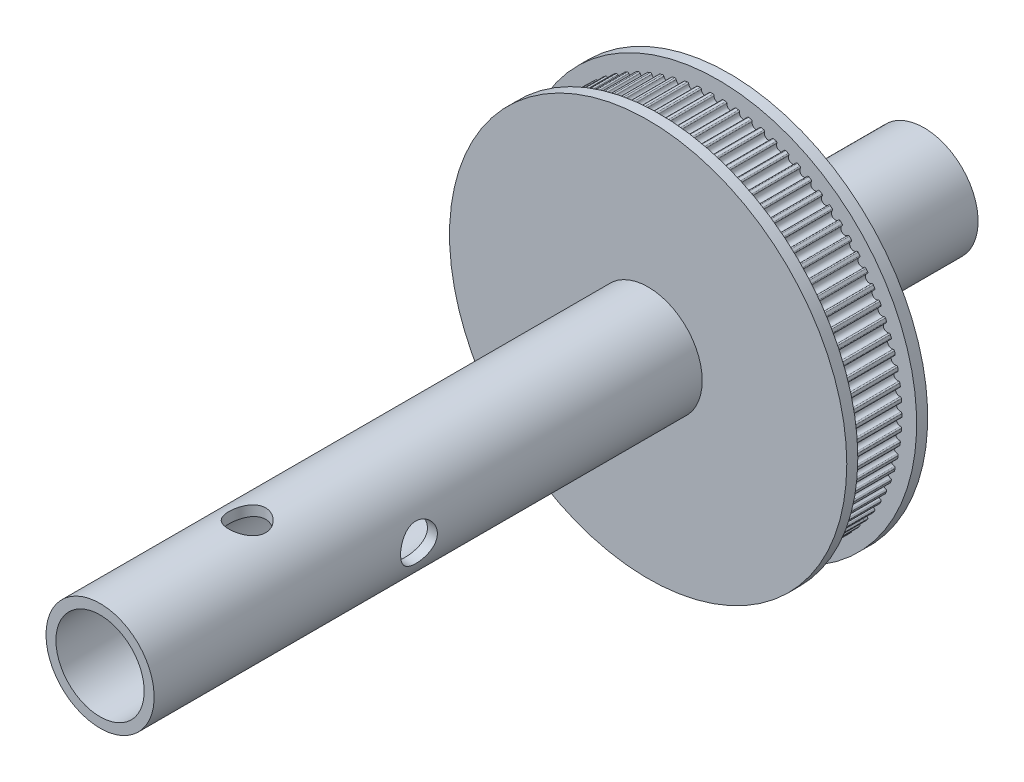
SolidWorks part; units mm, degrees
ref_plane "Ön Düzlem" through (0, 0, 0) normal (0, 0, 1) x (1, 0, 0)
ref_plane "Üst Düzlem" through (0, 0, 0) normal (0, 1, 0) x (1, 0, 0)
ref_plane "Sağ Düzlem" through (0, 0, 0) normal (1, 0, 0) x (0, 0, -1)
sketch "Çizim1" plane through (0, 0, 0) normal (0, 0, 1) x (1, 0, 0)
  arc A2 (0, 111.23) -> (2.457, 113.8116) centre (0, 113.69) ccw
  arc A3 (5.4881, 113.7058) -> (7.759, 110.959) centre (7.9306, 113.4131) ccw
  arc A4 (3.1755, 114.546) -> (2.457, 113.8116) centre (3.1561, 113.8463) ccw
  arc A5 (5.4881, 113.7058) -> (4.8225, 114.4885) centre (4.7931, 113.7891) ccw
  arc A6 (4.8225, 114.4885) -> (3.1755, 114.546) centre (0, 0) ccw
  arc A7 (7.759, 110.959) -> (10.3901, 113.363) centre (7.9306, 113.4131) ccw
  arc A8 (11.1581, 114.0454) -> (10.3901, 113.363) centre (11.09, 113.3488) ccw
  arc A9 (12.7971, 113.8732) -> (11.1581, 114.0454) centre (0, 0) ccw
  arc A10 (13.4064, 113.046) -> (12.7971, 113.8732) centre (12.7189, 113.1776) ccw
  arc A11 (13.4064, 113.046) -> (15.4802, 110.1475) centre (15.8226, 112.5836) ccw
  arc A12 (15.4802, 110.1475) -> (18.2726, 112.3621) centre (15.8226, 112.5836) ccw
  arc A13 (19.0863, 112.9893) -> (18.2726, 112.3621) centre (18.9698, 112.2991) ccw
  arc A14 (20.7093, 112.7031) -> (19.0863, 112.9893) centre (0, 0) ccw
  arc A15 (21.2595, 111.8354) -> (20.7093, 112.7031) centre (20.5828, 112.0146) ccw
  arc A16 (21.2595, 111.8354) -> (23.126, 108.7994) centre (23.6375, 111.2056) ccw
  arc A17 (23.126, 108.7994) -> (26.0661, 110.8138) centre (23.6375, 111.2056) ccw
  arc A18 (26.9216, 111.3827) -> (26.0661, 110.8138) centre (26.7571, 110.7022) ccw
  arc A19 (28.5206, 110.984) -> (26.9216, 111.3827) centre (0, 0) ccw
  arc A20 (29.0089, 110.08) -> (28.5206, 110.984) centre (28.3464, 110.306) ccw
  arc A21 (29.0089, 110.08) -> (30.6591, 106.9211) centre (31.3372, 109.2858) ccw
  arc A22 (30.6591, 106.9211) -> (33.7326, 108.7255) centre (31.3372, 109.2858) ccw
  arc A23 (34.6257, 109.2334) -> (33.7326, 108.7255) centre (34.4142, 108.5661) ccw
  arc A24 (36.193, 108.7241) -> (34.6257, 109.2334) centre (0, 0) ccw
  arc A25 (36.6171, 107.7883) -> (36.193, 108.7241) centre (35.9719, 108.06) ccw
  arc A26 (36.6171, 107.7883) -> (38.0429, 104.522) centre (38.8843, 106.8337) ccw
  arc A27 (38.0429, 104.522) -> (41.2347, 106.1076) centre (38.8843, 106.8337) ccw
  arc A28 (42.1611, 106.5519) -> (41.2347, 106.1076) centre (41.9035, 105.901) ccw
  arc A29 (43.6891, 105.9346) -> (42.1611, 106.5519) centre (0, 0) ccw
  arc A30 (44.0468, 104.9715) -> (43.6891, 105.9346) centre (43.4222, 105.2874) ccw
  arc A31 (44.0468, 104.9715) -> (45.2413, 101.6137) centre (46.2419, 103.861) ccw
  arc A32 (45.2413, 101.6137) -> (48.5359, 102.9728) centre (46.2419, 103.861) ccw
  arc A33 (49.491, 103.3514) -> (48.5359, 102.9728) centre (49.1887, 102.72) ccw
  arc A34 (50.9723, 102.6289) -> (49.491, 103.3514) centre (0, 0) ccw
  arc A35 (51.2619, 101.6432) -> (50.9723, 102.6289) centre (50.6609, 102.002) ccw
  arc A36 (51.2619, 101.6432) -> (52.2193, 98.2103) centre (53.3742, 100.3823) ccw
  arc A37 (52.2193, 98.2103) -> (55.6007, 99.3362) centre (53.3742, 100.3823) ccw
  arc A38 (56.5799, 99.6473) -> (55.6007, 99.3362) centre (56.2343, 99.0386) ccw
  arc A39 (58.0071, 98.8233) -> (56.5799, 99.6473) centre (0, 0) ccw
  arc A40 (58.2273, 97.8198) -> (58.0071, 98.8233) centre (57.6528, 98.2196) ccw
  arc A41 (58.2273, 97.8198) -> (58.9429, 94.3284) centre (60.2465, 96.4146) ccw
  arc A42 (58.9429, 94.3284) -> (62.3946, 95.2157) centre (60.2465, 96.4146) ccw
  arc A43 (63.3931, 95.4577) -> (62.3946, 95.2157) centre (63.0059, 94.8746) ccw
  arc A44 (64.7594, 94.5362) -> (63.3931, 95.4577) centre (0, 0) ccw
  arc A45 (64.9091, 93.5197) -> (64.7594, 94.5362) centre (64.3638, 93.9587) ccw
  arc A46 (64.9091, 93.5197) -> (65.3794, 89.987) centre (66.8253, 91.9771) ccw
  arc A47 (65.3794, 89.987) -> (68.8846, 90.6314) centre (66.8253, 91.9771) ccw
  arc A48 (69.8975, 90.8031) -> (68.8846, 90.6314) centre (69.4705, 90.2484) ccw
  arc A49 (71.1961, 89.7885) -> (69.8975, 90.8031) centre (0, 0) ccw
  arc A50 (71.2746, 88.7641) -> (71.1961, 89.7885) centre (70.7612, 89.24) ccw
  arc A51 (71.2746, 88.7641) -> (71.4973, 85.2071) centre (73.0785, 87.0916) ccw
  arc A52 (71.4973, 85.2071) -> (75.0389, 85.6055) centre (73.0785, 87.0916) ccw
  arc A53 (76.0613, 85.7061) -> (75.0389, 85.6055) centre (75.5967, 85.1826) ccw
  arc A54 (77.286, 84.6034) -> (76.0613, 85.7061) centre (0, 0) ccw
  arc A55 (77.2928, 83.576) -> (77.286, 84.6034) centre (76.8139, 84.0866) ccw
  arc A56 (77.2928, 83.576) -> (77.2669, 80.0122) centre (78.9757, 81.7817) ccw
  arc A57 (77.2669, 80.0122) -> (80.8276, 80.1625) centre (78.9757, 81.7817) ccw
  arc A58 (81.8546, 80.1916) -> (80.8276, 80.1625) centre (81.3546, 79.7017) ccw
  arc A59 (82.9994, 79.0061) -> (81.8546, 80.1916) centre (0, 0) ccw
  arc A60 (82.9345, 77.9808) -> (82.9994, 79.0061) centre (82.4924, 78.5235) ccw
  arc A61 (82.9345, 77.9808) -> (82.66, 74.4274) centre (84.4881, 76.0735) ccw
  arc A62 (82.66, 74.4274) -> (86.2226, 74.329) centre (84.4881, 76.0735) ccw
  arc A63 (87.2491, 74.2863) -> (86.2226, 74.329) centre (86.7161, 73.8326) ccw
  arc A64 (88.3084, 73.0239) -> (87.2491, 74.2863) centre (0, 0) ccw
  arc A65 (88.1721, 72.0056) -> (88.3084, 73.0239) centre (87.769, 72.5778) ccw
  arc A66 (88.1721, 72.0056) -> (87.6504, 68.48) centre (89.5889, 69.9946) ccw
  arc A67 (87.6504, 68.48) -> (91.1975, 68.1333) centre (89.5889, 69.9946) ccw
  arc A68 (92.2185, 68.0192) -> (91.1975, 68.1333) centre (91.6552, 67.6037) ccw
  arc A69 (93.1872, 66.6859) -> (92.2185, 68.0192) centre (0, 0) ccw
  arc A70 (92.9802, 65.6796) -> (93.1872, 66.6859) centre (92.6179, 66.2786) ccw
  arc A71 (92.9802, 65.6796) -> (92.2138, 62.199) centre (94.2533, 63.5746) ccw
  arc A72 (92.2138, 62.199) -> (95.7281, 61.6057) centre (94.2533, 63.5746) ccw
  arc A73 (96.7387, 61.4207) -> (95.7281, 61.6057) centre (96.1477, 61.0455) ccw
  arc A74 (97.612, 60.0231) -> (96.7387, 61.4207) centre (0, 0) ccw
  arc A75 (97.3353, 59.0336) -> (97.612, 60.0231) centre (97.0157, 59.6564) ccw
  arc A76 (97.3353, 59.0336) -> (96.328, 55.615) centre (98.4584, 56.845) ccw
  arc A77 (96.328, 55.615) -> (99.7923, 54.778) centre (98.4584, 56.845) ccw
  arc A78 (100.7875, 54.5229) -> (99.7923, 54.778) centre (100.1718, 54.1898) ccw
  arc A79 (101.5612, 53.0678) -> (100.7875, 54.5229) centre (0, 0) ccw
  arc A80 (101.2162, 52.1001) -> (101.5612, 53.0678) centre (100.9408, 52.7436) ccw
  arc A81 (101.2162, 52.1001) -> (99.9729, 48.76) centre (102.1839, 49.8384) ccw
  arc A82 (99.9729, 48.76) -> (103.3703, 47.6834) centre (102.1839, 49.8384) ccw
  arc A83 (104.3453, 47.3595) -> (103.3703, 47.6834) centre (103.7079, 47.0702) ccw
  arc A84 (105.0156, 45.854) -> (104.3453, 47.3595) centre (0, 0) ccw
  arc A85 (104.6039, 44.9127) -> (105.0156, 45.854) centre (104.3741, 45.5739) ccw
  arc A86 (104.6039, 44.9127) -> (103.1307, 41.6675) centre (105.4115, 42.589) ccw
  arc A87 (103.1307, 41.6675) -> (106.4447, 40.3565) centre (105.4115, 42.589) ccw
  arc A88 (107.3948, 39.9654) -> (106.4447, 40.3565) centre (106.7387, 39.7212) ccw
  arc A89 (107.9584, 38.4168) -> (107.3948, 39.9654) centre (0, 0) ccw
  arc A90 (107.4821, 37.5065) -> (107.9584, 38.4168) centre (107.2989, 38.1821) ccw
  arc A91 (107.4821, 37.5065) -> (105.786, 34.372) centre (108.1256, 35.1321) ccw
  arc A92 (105.786, 34.372) -> (109.0006, 32.833) centre (108.1256, 35.1321) ccw
  arc A93 (109.921, 32.3765) -> (109.0006, 32.833) centre (109.2495, 32.1788) ccw
  arc A94 (110.3753, 30.7924) -> (109.921, 32.3765) centre (0, 0) ccw
  arc A95 (109.8366, 29.9175) -> (110.3753, 30.7924) centre (109.701, 30.6043) ccw
  arc A96 (109.8366, 29.9175) -> (107.926, 26.909) centre (110.3129, 27.5041) ccw
  arc A97 (107.926, 26.909) -> (111.0254, 25.1495) centre (110.3129, 27.5041) ccw
  arc A98 (111.9117, 24.63) -> (111.0254, 25.1495) centre (111.2281, 24.4795) ccw
  arc A99 (112.2544, 23.018) -> (111.9117, 24.63) centre (0, 0) ccw
  arc A100 (111.6559, 22.1828) -> (112.2544, 23.018) centre (111.5686, 22.8774) ccw
  arc A101 (111.6559, 22.1828) -> (109.5402, 19.3149) centre (111.9628, 19.7421) ccw
  arc A102 (109.5402, 19.3149) -> (112.5092, 17.3435) centre (111.9628, 19.7421) ccw
  arc A103 (113.3572, 16.7634) -> (112.5092, 17.3435) centre (112.6647, 16.661) ccw
  arc A104 (113.5866, 15.1315) -> (113.3572, 16.7634) centre (0, 0) ccw
  arc A105 (112.9313, 14.3401) -> (113.5866, 15.1315) centre (112.8927, 15.039) ccw
  arc A106 (112.9313, 14.3401) -> (110.6207, 11.6267) centre (113.0672, 11.8838) ccw
  arc A107 (110.6207, 11.6267) -> (113.445, 9.453) centre (113.0672, 11.8838) ccw
  arc A108 (114.2504, 8.8152) -> (113.445, 9.453) centre (113.5525, 8.7613) ccw
  arc A109 (114.3654, 7.1712) -> (114.2504, 8.8152) centre (0, 0) ccw
  arc A110 (113.6566, 6.4275) -> (114.3654, 7.1712) centre (113.6668, 7.1274) ccw
  arc A111 (113.6566, 6.4275) -> (111.1622, 3.8819) centre (113.6207, 3.9677) ccw
  arc A112 (111.1622, 3.8819) -> (113.8281, 1.5165) centre (113.6207, 3.9677) ccw
  arc A113 (114.587, 0.824) -> (113.8281, 1.5165) centre (113.8871, 0.819) ccw
  arc A114 (114.587, -0.824) -> (114.587, 0.824) centre (0, 0) ccw
  arc A115 (113.8281, -1.5165) -> (114.587, -0.824) centre (113.8871, -0.819) ccw
  arc A116 (113.8281, -1.5165) -> (111.1622, -3.8819) centre (113.6207, -3.9677) ccw
  arc A117 (111.1622, -3.8819) -> (113.6566, -6.4275) centre (113.6207, -3.9677) ccw
  arc A118 (114.3654, -7.1712) -> (113.6566, -6.4275) centre (113.6668, -7.1274) ccw
  arc A119 (114.2504, -8.8152) -> (114.3654, -7.1712) centre (0, 0) ccw
  arc A120 (113.445, -9.453) -> (114.2504, -8.8152) centre (113.5525, -8.7613) ccw
  arc A121 (113.445, -9.453) -> (110.6207, -11.6267) centre (113.0672, -11.8838) ccw
  arc A122 (110.6207, -11.6267) -> (112.9313, -14.3401) centre (113.0672, -11.8838) ccw
  arc A123 (113.5866, -15.1315) -> (112.9313, -14.3401) centre (112.8927, -15.039) ccw
  arc A124 (113.3572, -16.7634) -> (113.5866, -15.1315) centre (0, 0) ccw
  arc A125 (112.5092, -17.3435) -> (113.3572, -16.7634) centre (112.6647, -16.661) ccw
  arc A126 (112.5092, -17.3435) -> (109.5402, -19.3149) centre (111.9628, -19.7421) ccw
  arc A127 (109.5402, -19.3149) -> (111.6559, -22.1828) centre (111.9628, -19.7421) ccw
  arc A128 (112.2544, -23.018) -> (111.6559, -22.1828) centre (111.5686, -22.8774) ccw
  arc A129 (111.9117, -24.63) -> (112.2544, -23.018) centre (0, 0) ccw
  arc A130 (111.0254, -25.1495) -> (111.9117, -24.63) centre (111.2281, -24.4795) ccw
  arc A131 (111.0254, -25.1495) -> (107.926, -26.909) centre (110.3129, -27.5041) ccw
  arc A132 (107.926, -26.909) -> (109.8366, -29.9175) centre (110.3129, -27.5041) ccw
  arc A133 (110.3753, -30.7924) -> (109.8366, -29.9175) centre (109.701, -30.6043) ccw
  arc A134 (109.921, -32.3765) -> (110.3753, -30.7924) centre (0, 0) ccw
  arc A135 (109.0006, -32.833) -> (109.921, -32.3765) centre (109.2495, -32.1788) ccw
  arc A136 (109.0006, -32.833) -> (105.786, -34.372) centre (108.1256, -35.1321) ccw
  arc A137 (105.786, -34.372) -> (107.4821, -37.5065) centre (108.1256, -35.1321) ccw
  arc A138 (107.9584, -38.4168) -> (107.4821, -37.5065) centre (107.2989, -38.1821) ccw
  arc A139 (107.3948, -39.9654) -> (107.9584, -38.4168) centre (0, 0) ccw
  arc A140 (106.4447, -40.3565) -> (107.3948, -39.9654) centre (106.7387, -39.7212) ccw
  arc A141 (106.4447, -40.3565) -> (103.1307, -41.6675) centre (105.4115, -42.589) ccw
  arc A142 (103.1307, -41.6675) -> (104.6039, -44.9127) centre (105.4115, -42.589) ccw
  arc A143 (105.0156, -45.854) -> (104.6039, -44.9127) centre (104.3741, -45.5739) ccw
  arc A144 (104.3453, -47.3595) -> (105.0156, -45.854) centre (0, 0) ccw
  arc A145 (103.3703, -47.6834) -> (104.3453, -47.3595) centre (103.7079, -47.0702) ccw
  arc A146 (103.3703, -47.6834) -> (99.9729, -48.76) centre (102.1839, -49.8384) ccw
  arc A147 (99.9729, -48.76) -> (101.2162, -52.1001) centre (102.1839, -49.8384) ccw
  arc A148 (101.5612, -53.0678) -> (101.2162, -52.1001) centre (100.9408, -52.7436) ccw
  arc A149 (100.7875, -54.5229) -> (101.5612, -53.0678) centre (0, 0) ccw
  arc A150 (99.7923, -54.778) -> (100.7875, -54.5229) centre (100.1718, -54.1898) ccw
  arc A151 (99.7923, -54.778) -> (96.328, -55.615) centre (98.4584, -56.845) ccw
  arc A152 (96.328, -55.615) -> (97.3353, -59.0336) centre (98.4584, -56.845) ccw
  arc A153 (97.612, -60.0231) -> (97.3353, -59.0336) centre (97.0157, -59.6564) ccw
  arc A154 (96.7387, -61.4207) -> (97.612, -60.0231) centre (0, 0) ccw
  arc A155 (95.7281, -61.6057) -> (96.7387, -61.4207) centre (96.1477, -61.0455) ccw
  arc A156 (95.7281, -61.6057) -> (92.2138, -62.199) centre (94.2533, -63.5746) ccw
  arc A157 (92.2138, -62.199) -> (92.9802, -65.6796) centre (94.2533, -63.5746) ccw
  arc A158 (93.1872, -66.6859) -> (92.9802, -65.6796) centre (92.6179, -66.2786) ccw
  arc A159 (92.2185, -68.0192) -> (93.1872, -66.6859) centre (0, 0) ccw
  arc A160 (91.1975, -68.1333) -> (92.2185, -68.0192) centre (91.6552, -67.6037) ccw
  arc A161 (91.1975, -68.1333) -> (87.6504, -68.48) centre (89.5889, -69.9946) ccw
  arc A162 (87.6504, -68.48) -> (88.1721, -72.0056) centre (89.5889, -69.9946) ccw
  arc A163 (88.3084, -73.0239) -> (88.1721, -72.0056) centre (87.769, -72.5778) ccw
  arc A164 (87.2491, -74.2863) -> (88.3084, -73.0239) centre (0, 0) ccw
  arc A165 (86.2226, -74.329) -> (87.2491, -74.2863) centre (86.7161, -73.8326) ccw
  arc A166 (86.2226, -74.329) -> (82.66, -74.4274) centre (84.4881, -76.0735) ccw
  arc A167 (82.66, -74.4274) -> (82.9345, -77.9808) centre (84.4881, -76.0735) ccw
  arc A168 (82.9994, -79.0061) -> (82.9345, -77.9808) centre (82.4924, -78.5235) ccw
  arc A169 (81.8546, -80.1916) -> (82.9994, -79.0061) centre (0, 0) ccw
  arc A170 (80.8276, -80.1625) -> (81.8546, -80.1916) centre (81.3546, -79.7017) ccw
  arc A171 (80.8276, -80.1625) -> (77.2669, -80.0122) centre (78.9757, -81.7817) ccw
  arc A172 (77.2669, -80.0122) -> (77.2928, -83.576) centre (78.9757, -81.7817) ccw
  arc A173 (77.286, -84.6034) -> (77.2928, -83.576) centre (76.8139, -84.0866) ccw
  arc A174 (76.0613, -85.7061) -> (77.286, -84.6034) centre (0, 0) ccw
  arc A175 (75.0389, -85.6055) -> (76.0613, -85.7061) centre (75.5967, -85.1826) ccw
  arc A176 (75.0389, -85.6055) -> (71.4973, -85.2071) centre (73.0785, -87.0916) ccw
  arc A177 (71.4973, -85.2071) -> (71.2746, -88.7641) centre (73.0785, -87.0916) ccw
  arc A178 (71.1961, -89.7885) -> (71.2746, -88.7641) centre (70.7612, -89.24) ccw
  arc A179 (69.8975, -90.8031) -> (71.1961, -89.7885) centre (0, 0) ccw
  arc A180 (68.8846, -90.6314) -> (69.8975, -90.8031) centre (69.4705, -90.2484) ccw
  arc A181 (68.8846, -90.6314) -> (65.3794, -89.987) centre (66.8253, -91.9771) ccw
  arc A182 (65.3794, -89.987) -> (64.9091, -93.5197) centre (66.8253, -91.9771) ccw
  arc A183 (64.7594, -94.5362) -> (64.9091, -93.5197) centre (64.3638, -93.9587) ccw
  arc A184 (63.3931, -95.4577) -> (64.7594, -94.5362) centre (0, 0) ccw
  arc A185 (62.3946, -95.2157) -> (63.3931, -95.4577) centre (63.0059, -94.8746) ccw
  arc A186 (62.3946, -95.2157) -> (58.9429, -94.3284) centre (60.2465, -96.4146) ccw
  arc A187 (58.9429, -94.3284) -> (58.2273, -97.8198) centre (60.2465, -96.4146) ccw
  arc A188 (58.0071, -98.8233) -> (58.2273, -97.8198) centre (57.6528, -98.2196) ccw
  arc A189 (56.5799, -99.6473) -> (58.0071, -98.8233) centre (0, 0) ccw
  arc A190 (55.6007, -99.3362) -> (56.5799, -99.6473) centre (56.2343, -99.0386) ccw
  arc A191 (55.6007, -99.3362) -> (52.2193, -98.2103) centre (53.3742, -100.3823) ccw
  arc A192 (52.2193, -98.2103) -> (51.2619, -101.6432) centre (53.3742, -100.3823) ccw
  arc A193 (50.9723, -102.6289) -> (51.2619, -101.6432) centre (50.6609, -102.002) ccw
  arc A194 (49.491, -103.3514) -> (50.9723, -102.6289) centre (0, 0) ccw
  arc A195 (48.5359, -102.9728) -> (49.491, -103.3514) centre (49.1887, -102.72) ccw
  arc A196 (48.5359, -102.9728) -> (45.2413, -101.6137) centre (46.2419, -103.861) ccw
  arc A197 (45.2413, -101.6137) -> (44.0468, -104.9715) centre (46.2419, -103.861) ccw
  arc A198 (43.6891, -105.9346) -> (44.0468, -104.9715) centre (43.4222, -105.2874) ccw
  arc A199 (42.1611, -106.5519) -> (43.6891, -105.9346) centre (0, 0) ccw
  arc A200 (41.2347, -106.1076) -> (42.1611, -106.5519) centre (41.9035, -105.901) ccw
  arc A201 (41.2347, -106.1076) -> (38.0429, -104.522) centre (38.8843, -106.8337) ccw
  arc A202 (38.0429, -104.522) -> (36.6171, -107.7883) centre (38.8843, -106.8337) ccw
  arc A203 (36.193, -108.7241) -> (36.6171, -107.7883) centre (35.9719, -108.06) ccw
  arc A204 (34.6257, -109.2334) -> (36.193, -108.7241) centre (0, 0) ccw
  arc A205 (33.7326, -108.7255) -> (34.6257, -109.2334) centre (34.4142, -108.5661) ccw
  arc A206 (33.7326, -108.7255) -> (30.6591, -106.9211) centre (31.3372, -109.2858) ccw
  arc A207 (30.6591, -106.9211) -> (29.0089, -110.08) centre (31.3372, -109.2858) ccw
  arc A208 (28.5206, -110.984) -> (29.0089, -110.08) centre (28.3464, -110.306) ccw
  arc A209 (26.9216, -111.3827) -> (28.5206, -110.984) centre (0, 0) ccw
  arc A210 (26.0661, -110.8138) -> (26.9216, -111.3827) centre (26.7571, -110.7022) ccw
  arc A211 (26.0661, -110.8138) -> (23.126, -108.7994) centre (23.6375, -111.2056) ccw
  arc A212 (23.126, -108.7994) -> (21.2595, -111.8354) centre (23.6375, -111.2056) ccw
  arc A213 (20.7093, -112.7031) -> (21.2595, -111.8354) centre (20.5828, -112.0146) ccw
  arc A214 (19.0863, -112.9893) -> (20.7093, -112.7031) centre (0, 0) ccw
  arc A215 (18.2726, -112.3621) -> (19.0863, -112.9893) centre (18.9698, -112.2991) ccw
  arc A216 (18.2726, -112.3621) -> (15.4802, -110.1475) centre (15.8226, -112.5836) ccw
  arc A217 (15.4802, -110.1475) -> (13.4064, -113.046) centre (15.8226, -112.5836) ccw
  arc A218 (12.7971, -113.8732) -> (13.4064, -113.046) centre (12.7189, -113.1776) ccw
  arc A219 (11.1581, -114.0454) -> (12.7971, -113.8732) centre (0, 0) ccw
  arc A220 (10.3901, -113.363) -> (11.1581, -114.0454) centre (11.09, -113.3488) ccw
  arc A221 (10.3901, -113.363) -> (7.759, -110.959) centre (7.9306, -113.4131) ccw
  arc A222 (7.759, -110.959) -> (5.4881, -113.7058) centre (7.9306, -113.4131) ccw
  arc A223 (4.8225, -114.4885) -> (5.4881, -113.7058) centre (4.7931, -113.7891) ccw
  arc A224 (3.1755, -114.546) -> (4.8225, -114.4885) centre (0, 0) ccw
  arc A225 (2.457, -113.8116) -> (3.1755, -114.546) centre (3.1561, -113.8463) ccw
  arc A226 (2.457, -113.8116) -> (0, -111.23) centre (0, -113.69) ccw
  arc A227 (0, -111.23) -> (-2.457, -113.8116) centre (0, -113.69) ccw
  arc A228 (-3.1755, -114.546) -> (-2.457, -113.8116) centre (-3.1561, -113.8463) ccw
  arc A229 (-4.8225, -114.4885) -> (-3.1755, -114.546) centre (0, 0) ccw
  arc A230 (-5.4881, -113.7058) -> (-4.8225, -114.4885) centre (-4.7931, -113.7891) ccw
  arc A231 (-5.4881, -113.7058) -> (-7.759, -110.959) centre (-7.9306, -113.4131) ccw
  arc A232 (-7.759, -110.959) -> (-10.3901, -113.363) centre (-7.9306, -113.4131) ccw
  arc A233 (-11.1581, -114.0454) -> (-10.3901, -113.363) centre (-11.09, -113.3488) ccw
  arc A234 (-12.7971, -113.8732) -> (-11.1581, -114.0454) centre (0, 0) ccw
  arc A235 (-13.4064, -113.046) -> (-12.7971, -113.8732) centre (-12.7189, -113.1776) ccw
  arc A236 (-13.4064, -113.046) -> (-15.4802, -110.1475) centre (-15.8226, -112.5836) ccw
  arc A237 (-15.4802, -110.1475) -> (-18.2726, -112.3621) centre (-15.8226, -112.5836) ccw
  arc A238 (-19.0863, -112.9893) -> (-18.2726, -112.3621) centre (-18.9698, -112.2991) ccw
  arc A239 (-20.7093, -112.7031) -> (-19.0863, -112.9893) centre (0, 0) ccw
  arc A240 (-21.2595, -111.8354) -> (-20.7093, -112.7031) centre (-20.5828, -112.0146) ccw
  arc A241 (-21.2595, -111.8354) -> (-23.126, -108.7994) centre (-23.6375, -111.2056) ccw
  arc A242 (-23.126, -108.7994) -> (-26.0661, -110.8138) centre (-23.6375, -111.2056) ccw
  arc A243 (-26.9216, -111.3827) -> (-26.0661, -110.8138) centre (-26.7571, -110.7022) ccw
  arc A244 (-28.5206, -110.984) -> (-26.9216, -111.3827) centre (0, 0) ccw
  arc A245 (-29.0089, -110.08) -> (-28.5206, -110.984) centre (-28.3464, -110.306) ccw
  arc A246 (-29.0089, -110.08) -> (-30.6591, -106.9211) centre (-31.3372, -109.2858) ccw
  arc A247 (-30.6591, -106.9211) -> (-33.7326, -108.7255) centre (-31.3372, -109.2858) ccw
  arc A248 (-34.6257, -109.2334) -> (-33.7326, -108.7255) centre (-34.4142, -108.5661) ccw
  arc A249 (-36.193, -108.7241) -> (-34.6257, -109.2334) centre (0, 0) ccw
  arc A250 (-36.6171, -107.7883) -> (-36.193, -108.7241) centre (-35.9719, -108.06) ccw
  arc A251 (-36.6171, -107.7883) -> (-38.0429, -104.522) centre (-38.8843, -106.8337) ccw
  arc A252 (-38.0429, -104.522) -> (-41.2347, -106.1076) centre (-38.8843, -106.8337) ccw
  arc A253 (-42.1611, -106.5519) -> (-41.2347, -106.1076) centre (-41.9035, -105.901) ccw
  arc A254 (-43.6891, -105.9346) -> (-42.1611, -106.5519) centre (0, 0) ccw
  arc A255 (-44.0468, -104.9715) -> (-43.6891, -105.9346) centre (-43.4222, -105.2874) ccw
  arc A256 (-44.0468, -104.9715) -> (-45.2413, -101.6137) centre (-46.2419, -103.861) ccw
  arc A257 (-45.2413, -101.6137) -> (-48.5359, -102.9728) centre (-46.2419, -103.861) ccw
  arc A258 (-49.491, -103.3514) -> (-48.5359, -102.9728) centre (-49.1887, -102.72) ccw
  arc A259 (-50.9723, -102.6289) -> (-49.491, -103.3514) centre (0, 0) ccw
  arc A260 (-51.2619, -101.6432) -> (-50.9723, -102.6289) centre (-50.6609, -102.002) ccw
  arc A261 (-51.2619, -101.6432) -> (-52.2193, -98.2103) centre (-53.3742, -100.3823) ccw
  arc A262 (-52.2193, -98.2103) -> (-55.6007, -99.3362) centre (-53.3742, -100.3823) ccw
  arc A263 (-56.5799, -99.6473) -> (-55.6007, -99.3362) centre (-56.2343, -99.0386) ccw
  arc A264 (-58.0071, -98.8233) -> (-56.5799, -99.6473) centre (0, 0) ccw
  arc A265 (-58.2273, -97.8198) -> (-58.0071, -98.8233) centre (-57.6528, -98.2196) ccw
  arc A266 (-58.2273, -97.8198) -> (-58.9429, -94.3284) centre (-60.2465, -96.4146) ccw
  arc A267 (-58.9429, -94.3284) -> (-62.3946, -95.2157) centre (-60.2465, -96.4146) ccw
  arc A268 (-63.3931, -95.4577) -> (-62.3946, -95.2157) centre (-63.0059, -94.8746) ccw
  arc A269 (-64.7594, -94.5362) -> (-63.3931, -95.4577) centre (0, 0) ccw
  arc A270 (-64.9091, -93.5197) -> (-64.7594, -94.5362) centre (-64.3638, -93.9587) ccw
  arc A271 (-64.9091, -93.5197) -> (-65.3794, -89.987) centre (-66.8253, -91.9771) ccw
  arc A272 (-65.3794, -89.987) -> (-68.8846, -90.6314) centre (-66.8253, -91.9771) ccw
  arc A273 (-69.8975, -90.8031) -> (-68.8846, -90.6314) centre (-69.4705, -90.2484) ccw
  arc A274 (-71.1961, -89.7885) -> (-69.8975, -90.8031) centre (0, 0) ccw
  arc A275 (-71.2746, -88.7641) -> (-71.1961, -89.7885) centre (-70.7612, -89.24) ccw
  arc A276 (-71.2746, -88.7641) -> (-71.4973, -85.2071) centre (-73.0785, -87.0916) ccw
  arc A277 (-71.4973, -85.2071) -> (-75.0389, -85.6055) centre (-73.0785, -87.0916) ccw
  arc A278 (-76.0613, -85.7061) -> (-75.0389, -85.6055) centre (-75.5967, -85.1826) ccw
  arc A279 (-77.286, -84.6034) -> (-76.0613, -85.7061) centre (0, 0) ccw
  arc A280 (-77.2928, -83.576) -> (-77.286, -84.6034) centre (-76.8139, -84.0866) ccw
  arc A281 (-77.2928, -83.576) -> (-77.2669, -80.0122) centre (-78.9757, -81.7817) ccw
  arc A282 (-77.2669, -80.0122) -> (-80.8276, -80.1625) centre (-78.9757, -81.7817) ccw
  arc A283 (-81.8546, -80.1916) -> (-80.8276, -80.1625) centre (-81.3546, -79.7017) ccw
  arc A284 (-82.9994, -79.0061) -> (-81.8546, -80.1916) centre (0, 0) ccw
  arc A285 (-82.9345, -77.9808) -> (-82.9994, -79.0061) centre (-82.4924, -78.5235) ccw
  arc A286 (-82.9345, -77.9808) -> (-82.66, -74.4274) centre (-84.4881, -76.0735) ccw
  arc A287 (-82.66, -74.4274) -> (-86.2226, -74.329) centre (-84.4881, -76.0735) ccw
  arc A288 (-87.2491, -74.2863) -> (-86.2226, -74.329) centre (-86.7161, -73.8326) ccw
  arc A289 (-88.3084, -73.0239) -> (-87.2491, -74.2863) centre (0, 0) ccw
  arc A290 (-88.1721, -72.0056) -> (-88.3084, -73.0239) centre (-87.769, -72.5778) ccw
  arc A291 (-88.1721, -72.0056) -> (-87.6504, -68.48) centre (-89.5889, -69.9946) ccw
  arc A292 (-87.6504, -68.48) -> (-91.1975, -68.1333) centre (-89.5889, -69.9946) ccw
  arc A293 (-92.2185, -68.0192) -> (-91.1975, -68.1333) centre (-91.6552, -67.6037) ccw
  arc A294 (-93.1872, -66.6859) -> (-92.2185, -68.0192) centre (0, 0) ccw
  arc A295 (-92.9802, -65.6796) -> (-93.1872, -66.6859) centre (-92.6179, -66.2786) ccw
  arc A296 (-92.9802, -65.6796) -> (-92.2138, -62.199) centre (-94.2533, -63.5746) ccw
  arc A297 (-92.2138, -62.199) -> (-95.7281, -61.6057) centre (-94.2533, -63.5746) ccw
  arc A298 (-96.7387, -61.4207) -> (-95.7281, -61.6057) centre (-96.1477, -61.0455) ccw
  arc A299 (-97.612, -60.0231) -> (-96.7387, -61.4207) centre (0, 0) ccw
  arc A300 (-97.3353, -59.0336) -> (-97.612, -60.0231) centre (-97.0157, -59.6564) ccw
  arc A301 (-97.3353, -59.0336) -> (-96.328, -55.615) centre (-98.4584, -56.845) ccw
  arc A302 (-96.328, -55.615) -> (-99.7923, -54.778) centre (-98.4584, -56.845) ccw
  arc A303 (-100.7875, -54.5229) -> (-99.7923, -54.778) centre (-100.1718, -54.1898) ccw
  arc A304 (-101.5612, -53.0678) -> (-100.7875, -54.5229) centre (0, 0) ccw
  arc A305 (-101.2162, -52.1001) -> (-101.5612, -53.0678) centre (-100.9408, -52.7436) ccw
  arc A306 (-101.2162, -52.1001) -> (-99.9729, -48.76) centre (-102.1839, -49.8384) ccw
  arc A307 (-99.9729, -48.76) -> (-103.3703, -47.6834) centre (-102.1839, -49.8384) ccw
  arc A308 (-104.3453, -47.3595) -> (-103.3703, -47.6834) centre (-103.7079, -47.0702) ccw
  arc A309 (-105.0156, -45.854) -> (-104.3453, -47.3595) centre (0, 0) ccw
  arc A310 (-104.6039, -44.9127) -> (-105.0156, -45.854) centre (-104.3741, -45.5739) ccw
  arc A311 (-104.6039, -44.9127) -> (-103.1307, -41.6675) centre (-105.4115, -42.589) ccw
  arc A312 (-103.1307, -41.6675) -> (-106.4447, -40.3565) centre (-105.4115, -42.589) ccw
  arc A313 (-107.3948, -39.9654) -> (-106.4447, -40.3565) centre (-106.7387, -39.7212) ccw
  arc A314 (-107.9584, -38.4168) -> (-107.3948, -39.9654) centre (0, 0) ccw
  arc A315 (-107.4821, -37.5065) -> (-107.9584, -38.4168) centre (-107.2989, -38.1821) ccw
  arc A316 (-107.4821, -37.5065) -> (-105.786, -34.372) centre (-108.1256, -35.1321) ccw
  arc A317 (-105.786, -34.372) -> (-109.0006, -32.833) centre (-108.1256, -35.1321) ccw
  arc A318 (-109.921, -32.3765) -> (-109.0006, -32.833) centre (-109.2495, -32.1788) ccw
  arc A319 (-110.3753, -30.7924) -> (-109.921, -32.3765) centre (0, 0) ccw
  arc A320 (-109.8366, -29.9175) -> (-110.3753, -30.7924) centre (-109.701, -30.6043) ccw
  arc A321 (-109.8366, -29.9175) -> (-107.926, -26.909) centre (-110.3129, -27.5041) ccw
  arc A322 (-107.926, -26.909) -> (-111.0254, -25.1495) centre (-110.3129, -27.5041) ccw
  arc A323 (-111.9117, -24.63) -> (-111.0254, -25.1495) centre (-111.2281, -24.4795) ccw
  arc A324 (-112.2544, -23.018) -> (-111.9117, -24.63) centre (0, 0) ccw
  arc A325 (-111.6559, -22.1828) -> (-112.2544, -23.018) centre (-111.5686, -22.8774) ccw
  arc A326 (-111.6559, -22.1828) -> (-109.5402, -19.3149) centre (-111.9628, -19.7421) ccw
  arc A327 (-109.5402, -19.3149) -> (-112.5092, -17.3435) centre (-111.9628, -19.7421) ccw
  arc A328 (-113.3572, -16.7634) -> (-112.5092, -17.3435) centre (-112.6647, -16.661) ccw
  arc A329 (-113.5866, -15.1315) -> (-113.3572, -16.7634) centre (0, 0) ccw
  arc A330 (-112.9313, -14.3401) -> (-113.5866, -15.1315) centre (-112.8927, -15.039) ccw
  arc A331 (-112.9313, -14.3401) -> (-110.6207, -11.6267) centre (-113.0672, -11.8838) ccw
  arc A332 (-110.6207, -11.6267) -> (-113.445, -9.453) centre (-113.0672, -11.8838) ccw
  arc A333 (-114.2504, -8.8152) -> (-113.445, -9.453) centre (-113.5525, -8.7613) ccw
  arc A334 (-114.3654, -7.1712) -> (-114.2504, -8.8152) centre (0, 0) ccw
  arc A335 (-113.6566, -6.4275) -> (-114.3654, -7.1712) centre (-113.6668, -7.1274) ccw
  arc A336 (-113.6566, -6.4275) -> (-111.1622, -3.8819) centre (-113.6207, -3.9677) ccw
  arc A337 (-111.1622, -3.8819) -> (-113.8281, -1.5165) centre (-113.6207, -3.9677) ccw
  arc A338 (-114.587, -0.824) -> (-113.8281, -1.5165) centre (-113.8871, -0.819) ccw
  arc A339 (-114.587, 0.824) -> (-114.587, -0.824) centre (0, 0) ccw
  arc A340 (-113.8281, 1.5165) -> (-114.587, 0.824) centre (-113.8871, 0.819) ccw
  arc A341 (-113.8281, 1.5165) -> (-111.1622, 3.8819) centre (-113.6207, 3.9677) ccw
  arc A342 (-111.1622, 3.8819) -> (-113.6566, 6.4275) centre (-113.6207, 3.9677) ccw
  arc A343 (-114.3654, 7.1712) -> (-113.6566, 6.4275) centre (-113.6668, 7.1274) ccw
  arc A344 (-114.2504, 8.8152) -> (-114.3654, 7.1712) centre (0, 0) ccw
  arc A345 (-113.445, 9.453) -> (-114.2504, 8.8152) centre (-113.5525, 8.7613) ccw
  arc A346 (-113.445, 9.453) -> (-110.6207, 11.6267) centre (-113.0672, 11.8838) ccw
  arc A347 (-110.6207, 11.6267) -> (-112.9313, 14.3401) centre (-113.0672, 11.8838) ccw
  arc A348 (-113.5866, 15.1315) -> (-112.9313, 14.3401) centre (-112.8927, 15.039) ccw
  arc A349 (-113.3572, 16.7634) -> (-113.5866, 15.1315) centre (0, 0) ccw
  arc A350 (-112.5092, 17.3435) -> (-113.3572, 16.7634) centre (-112.6647, 16.661) ccw
  arc A351 (-112.5092, 17.3435) -> (-109.5402, 19.3149) centre (-111.9628, 19.7421) ccw
  arc A352 (-109.5402, 19.3149) -> (-111.6559, 22.1828) centre (-111.9628, 19.7421) ccw
  arc A353 (-112.2544, 23.018) -> (-111.6559, 22.1828) centre (-111.5686, 22.8774) ccw
  arc A354 (-111.9117, 24.63) -> (-112.2544, 23.018) centre (0, 0) ccw
  arc A355 (-111.0254, 25.1495) -> (-111.9117, 24.63) centre (-111.2281, 24.4795) ccw
  arc A356 (-111.0254, 25.1495) -> (-107.926, 26.909) centre (-110.3129, 27.5041) ccw
  arc A357 (-107.926, 26.909) -> (-109.8366, 29.9175) centre (-110.3129, 27.5041) ccw
  arc A358 (-110.3753, 30.7924) -> (-109.8366, 29.9175) centre (-109.701, 30.6043) ccw
  arc A359 (-109.921, 32.3765) -> (-110.3753, 30.7924) centre (0, 0) ccw
  arc A360 (-109.0006, 32.833) -> (-109.921, 32.3765) centre (-109.2495, 32.1788) ccw
  arc A361 (-109.0006, 32.833) -> (-105.786, 34.372) centre (-108.1256, 35.1321) ccw
  arc A362 (-105.786, 34.372) -> (-107.4821, 37.5065) centre (-108.1256, 35.1321) ccw
  arc A363 (-107.9584, 38.4168) -> (-107.4821, 37.5065) centre (-107.2989, 38.1821) ccw
  arc A364 (-107.3948, 39.9654) -> (-107.9584, 38.4168) centre (0, 0) ccw
  arc A365 (-106.4447, 40.3565) -> (-107.3948, 39.9654) centre (-106.7387, 39.7212) ccw
  arc A366 (-106.4447, 40.3565) -> (-103.1307, 41.6675) centre (-105.4115, 42.589) ccw
  arc A367 (-103.1307, 41.6675) -> (-104.6039, 44.9127) centre (-105.4115, 42.589) ccw
  arc A368 (-105.0156, 45.854) -> (-104.6039, 44.9127) centre (-104.3741, 45.5739) ccw
  arc A369 (-104.3453, 47.3595) -> (-105.0156, 45.854) centre (0, 0) ccw
  arc A370 (-103.3703, 47.6834) -> (-104.3453, 47.3595) centre (-103.7079, 47.0702) ccw
  arc A371 (-103.3703, 47.6834) -> (-99.9729, 48.76) centre (-102.1839, 49.8384) ccw
  arc A372 (-99.9729, 48.76) -> (-101.2162, 52.1001) centre (-102.1839, 49.8384) ccw
  arc A373 (-101.5612, 53.0678) -> (-101.2162, 52.1001) centre (-100.9408, 52.7436) ccw
  arc A374 (-100.7875, 54.5229) -> (-101.5612, 53.0678) centre (0, 0) ccw
  arc A375 (-99.7923, 54.778) -> (-100.7875, 54.5229) centre (-100.1718, 54.1898) ccw
  arc A376 (-99.7923, 54.778) -> (-96.328, 55.615) centre (-98.4584, 56.845) ccw
  arc A377 (-96.328, 55.615) -> (-97.3353, 59.0336) centre (-98.4584, 56.845) ccw
  arc A378 (-97.612, 60.0231) -> (-97.3353, 59.0336) centre (-97.0157, 59.6564) ccw
  arc A379 (-96.7387, 61.4207) -> (-97.612, 60.0231) centre (0, 0) ccw
  arc A380 (-95.7281, 61.6057) -> (-96.7387, 61.4207) centre (-96.1477, 61.0455) ccw
  arc A381 (-95.7281, 61.6057) -> (-92.2138, 62.199) centre (-94.2533, 63.5746) ccw
  arc A382 (-92.2138, 62.199) -> (-92.9802, 65.6796) centre (-94.2533, 63.5746) ccw
  arc A383 (-93.1872, 66.6859) -> (-92.9802, 65.6796) centre (-92.6179, 66.2786) ccw
  arc A384 (-92.2185, 68.0192) -> (-93.1872, 66.6859) centre (0, 0) ccw
  arc A385 (-91.1975, 68.1333) -> (-92.2185, 68.0192) centre (-91.6552, 67.6037) ccw
  arc A386 (-91.1975, 68.1333) -> (-87.6504, 68.48) centre (-89.5889, 69.9946) ccw
  arc A387 (-87.6504, 68.48) -> (-88.1721, 72.0056) centre (-89.5889, 69.9946) ccw
  arc A388 (-88.3084, 73.0239) -> (-88.1721, 72.0056) centre (-87.769, 72.5778) ccw
  arc A389 (-87.2491, 74.2863) -> (-88.3084, 73.0239) centre (0, 0) ccw
  arc A390 (-86.2226, 74.329) -> (-87.2491, 74.2863) centre (-86.7161, 73.8326) ccw
  arc A391 (-86.2226, 74.329) -> (-82.66, 74.4274) centre (-84.4881, 76.0735) ccw
  arc A392 (-82.66, 74.4274) -> (-82.9345, 77.9808) centre (-84.4881, 76.0735) ccw
  arc A393 (-82.9994, 79.0061) -> (-82.9345, 77.9808) centre (-82.4924, 78.5235) ccw
  arc A394 (-81.8546, 80.1916) -> (-82.9994, 79.0061) centre (0, 0) ccw
  arc A395 (-80.8276, 80.1625) -> (-81.8546, 80.1916) centre (-81.3546, 79.7017) ccw
  arc A396 (-80.8276, 80.1625) -> (-77.2669, 80.0122) centre (-78.9757, 81.7817) ccw
  arc A397 (-77.2669, 80.0122) -> (-77.2928, 83.576) centre (-78.9757, 81.7817) ccw
  arc A398 (-77.286, 84.6034) -> (-77.2928, 83.576) centre (-76.8139, 84.0866) ccw
  arc A399 (-76.0613, 85.7061) -> (-77.286, 84.6034) centre (0, 0) ccw
  arc A400 (-75.0389, 85.6055) -> (-76.0613, 85.7061) centre (-75.5967, 85.1826) ccw
  arc A401 (-75.0389, 85.6055) -> (-71.4973, 85.2071) centre (-73.0785, 87.0916) ccw
  arc A402 (-71.4973, 85.2071) -> (-71.2746, 88.7641) centre (-73.0785, 87.0916) ccw
  arc A403 (-71.1961, 89.7885) -> (-71.2746, 88.7641) centre (-70.7612, 89.24) ccw
  arc A404 (-69.8975, 90.8031) -> (-71.1961, 89.7885) centre (0, 0) ccw
  arc A405 (-68.8846, 90.6314) -> (-69.8975, 90.8031) centre (-69.4705, 90.2484) ccw
  arc A406 (-68.8846, 90.6314) -> (-65.3794, 89.987) centre (-66.8253, 91.9771) ccw
  arc A407 (-65.3794, 89.987) -> (-64.9091, 93.5197) centre (-66.8253, 91.9771) ccw
  arc A408 (-64.7594, 94.5362) -> (-64.9091, 93.5197) centre (-64.3638, 93.9587) ccw
  arc A409 (-63.3931, 95.4577) -> (-64.7594, 94.5362) centre (0, 0) ccw
  arc A410 (-62.3946, 95.2157) -> (-63.3931, 95.4577) centre (-63.0059, 94.8746) ccw
  arc A411 (-62.3946, 95.2157) -> (-58.9429, 94.3284) centre (-60.2465, 96.4146) ccw
  arc A412 (-58.9429, 94.3284) -> (-58.2273, 97.8198) centre (-60.2465, 96.4146) ccw
  arc A413 (-58.0071, 98.8233) -> (-58.2273, 97.8198) centre (-57.6528, 98.2196) ccw
  arc A414 (-56.5799, 99.6473) -> (-58.0071, 98.8233) centre (0, 0) ccw
  arc A415 (-55.6007, 99.3362) -> (-56.5799, 99.6473) centre (-56.2343, 99.0386) ccw
  arc A416 (-55.6007, 99.3362) -> (-52.2193, 98.2103) centre (-53.3742, 100.3823) ccw
  arc A417 (-52.2193, 98.2103) -> (-51.2619, 101.6432) centre (-53.3742, 100.3823) ccw
  arc A418 (-50.9723, 102.6289) -> (-51.2619, 101.6432) centre (-50.6609, 102.002) ccw
  arc A419 (-49.491, 103.3514) -> (-50.9723, 102.6289) centre (0, 0) ccw
  arc A420 (-48.5359, 102.9728) -> (-49.491, 103.3514) centre (-49.1887, 102.72) ccw
  arc A421 (-48.5359, 102.9728) -> (-45.2413, 101.6137) centre (-46.2419, 103.861) ccw
  arc A422 (-45.2413, 101.6137) -> (-44.0468, 104.9715) centre (-46.2419, 103.861) ccw
  arc A423 (-43.6891, 105.9346) -> (-44.0468, 104.9715) centre (-43.4222, 105.2874) ccw
  arc A424 (-42.1611, 106.5519) -> (-43.6891, 105.9346) centre (0, 0) ccw
  arc A425 (-41.2347, 106.1076) -> (-42.1611, 106.5519) centre (-41.9035, 105.901) ccw
  arc A426 (-41.2347, 106.1076) -> (-38.0429, 104.522) centre (-38.8843, 106.8337) ccw
  arc A427 (-38.0429, 104.522) -> (-36.6171, 107.7883) centre (-38.8843, 106.8337) ccw
  arc A428 (-36.193, 108.7241) -> (-36.6171, 107.7883) centre (-35.9719, 108.06) ccw
  arc A429 (-34.6257, 109.2334) -> (-36.193, 108.7241) centre (0, 0) ccw
  arc A430 (-33.7326, 108.7255) -> (-34.6257, 109.2334) centre (-34.4142, 108.5661) ccw
  arc A431 (-33.7326, 108.7255) -> (-30.6591, 106.9211) centre (-31.3372, 109.2858) ccw
  arc A432 (-30.6591, 106.9211) -> (-29.0089, 110.08) centre (-31.3372, 109.2858) ccw
  arc A433 (-28.5206, 110.984) -> (-29.0089, 110.08) centre (-28.3464, 110.306) ccw
  arc A434 (-26.9216, 111.3827) -> (-28.5206, 110.984) centre (0, 0) ccw
  arc A435 (-26.0661, 110.8138) -> (-26.9216, 111.3827) centre (-26.7571, 110.7022) ccw
  arc A436 (-26.0661, 110.8138) -> (-23.126, 108.7994) centre (-23.6375, 111.2056) ccw
  arc A437 (-23.126, 108.7994) -> (-21.2595, 111.8354) centre (-23.6375, 111.2056) ccw
  arc A438 (-20.7093, 112.7031) -> (-21.2595, 111.8354) centre (-20.5828, 112.0146) ccw
  arc A439 (-19.0863, 112.9893) -> (-20.7093, 112.7031) centre (0, 0) ccw
  arc A440 (-18.2726, 112.3621) -> (-19.0863, 112.9893) centre (-18.9698, 112.2991) ccw
  arc A441 (-18.2726, 112.3621) -> (-15.4802, 110.1475) centre (-15.8226, 112.5836) ccw
  arc A442 (-15.4802, 110.1475) -> (-13.4064, 113.046) centre (-15.8226, 112.5836) ccw
  arc A443 (-12.7971, 113.8732) -> (-13.4064, 113.046) centre (-12.7189, 113.1776) ccw
  arc A444 (-11.1581, 114.0454) -> (-12.7971, 113.8732) centre (0, 0) ccw
  arc A445 (-10.3901, 113.363) -> (-11.1581, 114.0454) centre (-11.09, 113.3488) ccw
  arc A446 (-10.3901, 113.363) -> (-7.759, 110.959) centre (-7.9306, 113.4131) ccw
  arc A447 (-7.759, 110.959) -> (-5.4881, 113.7058) centre (-7.9306, 113.4131) ccw
  arc A448 (-4.8225, 114.4885) -> (-5.4881, 113.7058) centre (-4.7931, 113.7891) ccw
  arc A449 (-3.1755, 114.546) -> (-4.8225, 114.4885) centre (0, 0) ccw
  arc A450 (-2.457, 113.8116) -> (-3.1755, 114.546) centre (-3.1561, 113.8463) ccw
  arc A451 (-2.457, 113.8116) -> (0, 111.23) centre (0, 113.69) ccw
  dimension "D1" = 90
  dimension "D3" = 4.92
  dimension "D4" = 4.92
  dimension "D5" = 1.4
  dimension "D6" = 1.4
extrude "Yükseklik-Ekstrüzyon1" add sketch "Çizim1" along normal blind 23
sketch "Çizim2" plane through (0, 0, 23) normal (0, 0, 1) x (1, 0, 0)
  circle A0 centre (0, 0) radius 45
  dimension "D1" = 90
extrude "Yükseklik-Ekstrüzyon2" add sketch "Çizim2" along normal blind 12
sketch "Çizim3" plane through (0, 0, 35) normal (0, 0, 1) x (1, 0, 0)
  circle A0 centre (0, 0) radius 10
  dimension "D1" = 20
extrude "Kes-Ekstrüzyon1" cut sketch "Çizim3" against normal blind 94
chamfer "Pah1" distance 1 angle 45 1 edges at (45, 0, 35)
scale "Scale1" scale about centroid uniform scaling yes scale factor 0.218169
sketch "Sketch4" plane through (0, 0, 15.0146) normal (0, 0, 1) x (1, 0, 0)
  circle A0 centre (0, 0) radius 9.8176
extrude "Cut-Extrude1" cut sketch "Sketch4" along normal through all
sketch "Sketch15" plane through (0, 0, 9.9967) normal (0, 0, -1) x (-1, 0, 0)
  arc A360 (-0.536, 24.8302) -> (-0.6928, 24.9904) centre (-0.6886, 24.8377) ccw
  arc A361 (-0.6928, 24.9904) -> (-1.0521, 24.9779) centre (0, 0) ccw
  arc A362 (-1.0521, 24.9779) -> (-1.1973, 24.8071) centre (-1.0457, 24.8253) ccw
  arc A363 (-2.2668, 24.7323) -> (-1.1973, 24.8071) centre (-1.7302, 24.7432) ccw
  arc A364 (-2.2668, 24.7323) -> (-2.4344, 24.8812) centre (-2.4195, 24.7292) ccw
  arc A365 (-2.4344, 24.8812) -> (-2.7919, 24.8436) centre (0, 0) ccw
  arc A366 (-2.7919, 24.8436) -> (-2.9249, 24.6631) centre (-2.7749, 24.6919) ccw
  arc A367 (-3.9865, 24.5139) -> (-2.9249, 24.6631) centre (-3.452, 24.5623) ccw
  arc A368 (-3.9865, 24.5139) -> (-4.1641, 24.6508) centre (-4.1386, 24.5002) ccw
  arc A369 (-4.1641, 24.6508) -> (-4.5181, 24.5883) centre (0, 0) ccw
  arc A370 (-4.5181, 24.5883) -> (-4.6382, 24.399) centre (-4.4905, 24.4381) ccw
  arc A371 (-5.6868, 24.1761) -> (-4.6382, 24.399) centre (-5.157, 24.2616) ccw
  arc A372 (-5.6868, 24.1761) -> (-5.8735, 24.3003) centre (-5.8376, 24.1518) ccw
  arc A373 (-5.8735, 24.3003) -> (-6.2223, 24.2133) centre (0, 0) ccw
  arc A374 (-6.2223, 24.2133) -> (-6.3289, 24.0161) centre (-6.1843, 24.0654) ccw
  arc A375 (-7.3594, 23.7206) -> (-6.3289, 24.0161) centre (-6.8368, 23.8428) ccw
  arc A376 (-7.3594, 23.7206) -> (-7.5543, 23.8314) centre (-7.5081, 23.6858) ccw
  arc A377 (-7.5543, 23.8314) -> (-7.8962, 23.7202) centre (0, 0) ccw
  arc A378 (-7.8962, 23.7202) -> (-7.9887, 23.5161) centre (-7.848, 23.5753) ccw
  arc A379 (-8.9961, 23.1494) -> (-7.9887, 23.5161) centre (-8.4833, 23.3078) ccw
  arc A380 (-8.9961, 23.1494) -> (-9.1982, 23.2463) centre (-9.1421, 23.1043) ccw
  arc A381 (-9.1982, 23.2463) -> (-9.5316, 23.1117) centre (0, 0) ccw
  arc A382 (-9.5316, 23.1117) -> (-9.6097, 22.9015) centre (-9.4734, 22.9705) ccw
  arc A383 (-10.589, 22.4655) -> (-9.6097, 22.9015) centre (-10.0886, 22.6593) ccw
  arc A384 (-10.589, 22.4655) -> (-10.7974, 22.5481) centre (-10.7315, 22.4103) ccw
  arc A385 (-10.7974, 22.5481) -> (-11.1206, 22.3905) centre (0, 0) ccw
  arc A386 (-11.1206, 22.3905) -> (-11.1838, 22.1754) centre (-11.0526, 22.2537) ccw
  arc A387 (-12.1304, 21.6721) -> (-11.1838, 22.1754) centre (-11.6446, 21.9003) ccw
  arc A388 (-12.1304, 21.6721) -> (-12.344, 21.74) centre (-12.2686, 21.6072) ccw
  arc A389 (-12.344, 21.74) -> (-12.6554, 21.5602) centre (0, 0) ccw
  arc A390 (-12.6554, 21.5602) -> (-12.7034, 21.3413) centre (-12.5781, 21.4285) ccw
  arc A391 (-13.6126, 20.7731) -> (-12.7034, 21.3413) centre (-13.1439, 21.0347) ccw
  arc A392 (-13.6126, 20.7731) -> (-13.8304, 20.8259) centre (-13.7459, 20.6987) ccw
  arc A393 (-13.8304, 20.8259) -> (-14.1285, 20.6249) centre (0, 0) ccw
  arc A394 (-14.1285, 20.6249) -> (-14.1612, 20.4031) centre (-14.0422, 20.4989) ccw
  arc A395 (-15.0285, 19.773) -> (-14.1612, 20.4031) centre (-14.5792, 20.0666) ccw
  arc A396 (-15.0285, 19.773) -> (-15.2495, 19.8104) centre (-15.1563, 19.6894) ccw
  arc A397 (-15.2495, 19.8104) -> (-15.5328, 19.5891) centre (0, 0) ccw
  arc A398 (-15.5328, 19.5891) -> (-15.5499, 19.3656) centre (-15.4379, 19.4694) ccw
  arc A399 (-16.3712, 18.6765) -> (-15.5499, 19.3656) centre (-15.9435, 19.0007) ccw
  arc A400 (-16.3712, 18.6765) -> (-16.5942, 18.6984) centre (-16.4929, 18.5842) ccw
  arc A401 (-16.5942, 18.6984) -> (-16.8614, 18.4578) centre (0, 0) ccw
  arc A402 (-16.8614, 18.4578) -> (-16.8629, 18.2337) centre (-16.7584, 18.3451) ccw
  arc A403 (-17.6341, 17.489) -> (-16.8629, 18.2337) centre (-17.2301, 17.8423) ccw
  arc A404 (-17.6341, 17.489) -> (-17.8582, 17.4953) centre (-17.7491, 17.3885) ccw
  arc A405 (-17.8582, 17.4953) -> (-18.1079, 17.2367) centre (0, 0) ccw
  arc A406 (-18.1079, 17.2367) -> (-18.0937, 17.013) centre (-17.9973, 17.1314) ccw
  arc A407 (-18.8111, 16.2163) -> (-18.0937, 17.013) centre (-18.4327, 16.5969) ccw
  arc A408 (-18.8111, 16.2163) -> (-19.0351, 16.207) centre (-18.9188, 16.108) ccw
  arc A409 (-19.0351, 16.207) -> (-19.2662, 15.9316) centre (0, 0) ccw
  arc A410 (-19.2662, 15.9316) -> (-19.2364, 15.7094) centre (-19.1485, 15.8342) ccw
  arc A411 (-19.8965, 14.8646) -> (-19.2364, 15.7094) centre (-19.5455, 15.2707) ccw
  arc A412 (-19.8965, 14.8646) -> (-20.1192, 14.8397) centre (-19.9963, 14.749) ccw
  arc A413 (-20.1192, 14.8397) -> (-20.3306, 14.5488) centre (0, 0) ccw
  arc A414 (-20.3306, 14.5488) -> (-20.2854, 14.3293) centre (-20.2064, 14.4599) ccw
  arc A415 (-20.8849, 13.4405) -> (-20.2854, 14.3293) centre (-20.5632, 13.87) ccw
  arc A416 (-20.8849, 13.4405) -> (-21.1054, 13.4001) centre (-20.9765, 13.3182) ccw
  arc A417 (-21.1054, 13.4001) -> (-21.2959, 13.0952) centre (0, 0) ccw
  arc A418 (-21.2959, 13.0952) -> (-21.2356, 12.8793) centre (-21.1658, 13.0152) ccw
  arc A419 (-21.7716, 11.9509) -> (-21.2356, 12.8793) centre (-21.4806, 12.4018) ccw
  arc A420 (-21.7716, 11.9509) -> (-21.9887, 11.8952) centre (-21.8544, 11.8225) ccw
  arc A421 (-21.9887, 11.8952) -> (-22.1575, 11.5778) centre (0, 0) ccw
  arc A422 (-22.1575, 11.5778) -> (-22.0822, 11.3666) centre (-22.0222, 11.507) ccw
  arc A423 (-22.5522, 10.403) -> (-22.0822, 11.3666) centre (-22.2934, 10.8732) ccw
  arc A424 (-22.5522, 10.403) -> (-22.7649, 10.3324) centre (-22.6259, 10.2693) ccw
  arc A425 (-22.7649, 10.3324) -> (-22.9112, 10.0039) centre (0, 0) ccw
  arc A426 (-22.9112, 10.0039) -> (-22.8213, 9.7986) centre (-22.7712, 9.9428) ccw
  arc A427 (-23.223, 8.8045) -> (-22.8213, 9.7986) centre (-22.9975, 9.2916) ccw
  arc A428 (-23.223, 8.8045) -> (-23.4302, 8.7192) centre (-23.2871, 8.6659) ccw
  arc A429 (-23.4302, 8.7192) -> (-23.5532, 8.3814) centre (0, 0) ccw
  arc A430 (-23.5532, 8.3814) -> (-23.4493, 8.1828) centre (-23.4093, 8.3302) ccw
  arc A431 (-23.7806, 7.1631) -> (-23.4493, 8.1828) centre (-23.5897, 7.6647) ccw
  arc A432 (-23.7806, 7.1631) -> (-23.9814, 7.0636) centre (-23.8349, 7.0204) ccw
  arc A433 (-23.9814, 7.0636) -> (-24.0805, 6.7179) centre (0, 0) ccw
  arc A434 (-24.0805, 6.7179) -> (-23.9629, 6.5271) centre (-23.9334, 6.6769) ccw
  arc A435 (-24.2223, 5.4868) -> (-23.9629, 6.5271) centre (-24.0669, 6.0005) ccw
  arc A436 (-24.2223, 5.4868) -> (-24.4157, 5.3735) centre (-24.2665, 5.3407) ccw
  arc A437 (-24.4157, 5.3735) -> (-24.4904, 5.0218) centre (0, 0) ccw
  arc A438 (-24.4904, 5.0218) -> (-24.3599, 4.8396) centre (-24.3408, 4.9911) ccw
  arc A439 (-24.546, 3.7838) -> (-24.3599, 4.8396) centre (-24.4268, 4.3071) ccw
  arc A440 (-24.546, 3.7838) -> (-24.731, 3.6573) centre (-24.58, 3.6349) ccw
  arc A441 (-24.731, 3.6573) -> (-24.7811, 3.3012) centre (0, 0) ccw
  arc A442 (-24.7811, 3.3012) -> (-24.6381, 3.1286) centre (-24.6297, 3.281) ccw
  arc A443 (-24.7502, 2.0624) -> (-24.6381, 3.1286) centre (-24.6678, 2.5927) ccw
  arc A444 (-24.7502, 2.0624) -> (-24.9259, 1.9232) centre (-24.7737, 1.9115) ccw
  arc A445 (-24.9259, 1.9232) -> (-24.951, 1.5645) centre (0, 0) ccw
  arc A446 (-24.951, 1.5645) -> (-24.7964, 1.4023) centre (-24.7986, 1.555) ccw
  arc A447 (-24.8338, 0.3308) -> (-24.7964, 1.4023) centre (-24.7885, 0.8656) ccw
  arc A448 (-24.8338, 0.3308) -> (-24.9994, 0.1798) centre (-24.8466, 0.1787) ccw
  arc A449 (-24.9994, 0.1798) -> (-24.9994, -0.1798) centre (0, 0) ccw
  arc A450 (-24.9994, -0.1798) -> (-24.8338, -0.3308) centre (-24.8466, -0.1787) ccw
  arc A451 (-24.7964, -1.4023) -> (-24.8338, -0.3308) centre (-24.7885, -0.8656) ccw
  arc A452 (-24.7964, -1.4023) -> (-24.951, -1.5645) centre (-24.7986, -1.555) ccw
  arc A453 (-24.951, -1.5645) -> (-24.9259, -1.9232) centre (0, 0) ccw
  arc A454 (-24.9259, -1.9232) -> (-24.7502, -2.0624) centre (-24.7737, -1.9115) ccw
  arc A455 (-24.6381, -3.1286) -> (-24.7502, -2.0624) centre (-24.6678, -2.5927) ccw
  arc A456 (-24.6381, -3.1286) -> (-24.7811, -3.3012) centre (-24.6297, -3.281) ccw
  arc A457 (-24.7811, -3.3012) -> (-24.731, -3.6573) centre (0, 0) ccw
  arc A458 (-24.731, -3.6573) -> (-24.546, -3.7838) centre (-24.58, -3.6349) ccw
  arc A459 (-24.3599, -4.8396) -> (-24.546, -3.7838) centre (-24.4268, -4.3071) ccw
  arc A460 (-24.3599, -4.8396) -> (-24.4904, -5.0218) centre (-24.3408, -4.9911) ccw
  arc A461 (-24.4904, -5.0218) -> (-24.4157, -5.3735) centre (0, 0) ccw
  arc A462 (-24.4157, -5.3735) -> (-24.2223, -5.4868) centre (-24.2665, -5.3407) ccw
  arc A463 (-23.9629, -6.5271) -> (-24.2223, -5.4868) centre (-24.0669, -6.0005) ccw
  arc A464 (-23.9629, -6.5271) -> (-24.0805, -6.7179) centre (-23.9334, -6.6769) ccw
  arc A465 (-24.0805, -6.7179) -> (-23.9814, -7.0636) centre (0, 0) ccw
  arc A466 (-23.9814, -7.0636) -> (-23.7806, -7.1631) centre (-23.8349, -7.0204) ccw
  arc A467 (-23.4493, -8.1828) -> (-23.7806, -7.1631) centre (-23.5897, -7.6647) ccw
  arc A468 (-23.4493, -8.1828) -> (-23.5532, -8.3814) centre (-23.4093, -8.3302) ccw
  arc A469 (-23.5532, -8.3814) -> (-23.4302, -8.7192) centre (0, 0) ccw
  arc A470 (-23.4302, -8.7192) -> (-23.223, -8.8045) centre (-23.2871, -8.6659) ccw
  arc A471 (-22.8213, -9.7986) -> (-23.223, -8.8045) centre (-22.9975, -9.2916) ccw
  arc A472 (-22.8213, -9.7986) -> (-22.9112, -10.0039) centre (-22.7712, -9.9428) ccw
  arc A473 (-22.9112, -10.0039) -> (-22.7649, -10.3324) centre (0, 0) ccw
  arc A474 (-22.7649, -10.3324) -> (-22.5522, -10.403) centre (-22.6259, -10.2693) ccw
  arc A475 (-22.0822, -11.3666) -> (-22.5522, -10.403) centre (-22.2934, -10.8732) ccw
  arc A476 (-22.0822, -11.3666) -> (-22.1575, -11.5778) centre (-22.0222, -11.507) ccw
  arc A477 (-22.1575, -11.5778) -> (-21.9887, -11.8952) centre (0, 0) ccw
  arc A478 (-21.9887, -11.8952) -> (-21.7716, -11.9509) centre (-21.8544, -11.8225) ccw
  arc A479 (-21.2356, -12.8793) -> (-21.7716, -11.9509) centre (-21.4806, -12.4018) ccw
  arc A480 (-21.2356, -12.8793) -> (-21.2959, -13.0952) centre (-21.1658, -13.0152) ccw
  arc A481 (-21.2959, -13.0952) -> (-21.1054, -13.4001) centre (0, 0) ccw
  arc A482 (-21.1054, -13.4001) -> (-20.8849, -13.4405) centre (-20.9765, -13.3182) ccw
  arc A483 (-20.2854, -14.3293) -> (-20.8849, -13.4405) centre (-20.5632, -13.87) ccw
  arc A484 (-20.2854, -14.3293) -> (-20.3306, -14.5488) centre (-20.2064, -14.4599) ccw
  arc A485 (-20.3306, -14.5488) -> (-20.1192, -14.8397) centre (0, 0) ccw
  arc A486 (-20.1192, -14.8397) -> (-19.8965, -14.8646) centre (-19.9963, -14.749) ccw
  arc A487 (-19.2364, -15.7094) -> (-19.8965, -14.8646) centre (-19.5455, -15.2707) ccw
  arc A488 (-19.2364, -15.7094) -> (-19.2662, -15.9316) centre (-19.1485, -15.8342) ccw
  arc A489 (-19.2662, -15.9316) -> (-19.0351, -16.207) centre (0, 0) ccw
  arc A490 (-19.0351, -16.207) -> (-18.8111, -16.2163) centre (-18.9188, -16.108) ccw
  arc A491 (-18.0937, -17.013) -> (-18.8111, -16.2163) centre (-18.4327, -16.5969) ccw
  arc A492 (-18.0937, -17.013) -> (-18.1079, -17.2367) centre (-17.9973, -17.1314) ccw
  arc A493 (-18.1079, -17.2367) -> (-17.8582, -17.4953) centre (0, 0) ccw
  arc A494 (-17.8582, -17.4953) -> (-17.6341, -17.489) centre (-17.7491, -17.3885) ccw
  arc A495 (-16.8629, -18.2337) -> (-17.6341, -17.489) centre (-17.2301, -17.8423) ccw
  arc A496 (-16.8629, -18.2337) -> (-16.8614, -18.4578) centre (-16.7584, -18.3451) ccw
  arc A497 (-16.8614, -18.4578) -> (-16.5942, -18.6984) centre (0, 0) ccw
  arc A498 (-16.5942, -18.6984) -> (-16.3712, -18.6765) centre (-16.4929, -18.5842) ccw
  arc A499 (-15.5499, -19.3656) -> (-16.3712, -18.6765) centre (-15.9435, -19.0007) ccw
  arc A500 (-15.5499, -19.3656) -> (-15.5328, -19.5891) centre (-15.4379, -19.4694) ccw
  arc A501 (-15.5328, -19.5891) -> (-15.2495, -19.8104) centre (0, 0) ccw
  arc A502 (-15.2495, -19.8104) -> (-15.0285, -19.773) centre (-15.1563, -19.6894) ccw
  arc A503 (-14.1612, -20.4031) -> (-15.0285, -19.773) centre (-14.5792, -20.0666) ccw
  arc A504 (-14.1612, -20.4031) -> (-14.1285, -20.6249) centre (-14.0422, -20.4989) ccw
  arc A505 (-14.1285, -20.6249) -> (-13.8304, -20.8259) centre (0, 0) ccw
  arc A506 (-13.8304, -20.8259) -> (-13.6126, -20.7731) centre (-13.7459, -20.6987) ccw
  arc A507 (-12.7034, -21.3413) -> (-13.6126, -20.7731) centre (-13.1439, -21.0347) ccw
  arc A508 (-12.7034, -21.3413) -> (-12.6554, -21.5602) centre (-12.5781, -21.4285) ccw
  arc A509 (-12.6554, -21.5602) -> (-12.344, -21.74) centre (0, 0) ccw
  arc A510 (-12.344, -21.74) -> (-12.1304, -21.6721) centre (-12.2686, -21.6072) ccw
  arc A511 (-11.1838, -22.1754) -> (-12.1304, -21.6721) centre (-11.6446, -21.9003) ccw
  arc A512 (-11.1838, -22.1754) -> (-11.1206, -22.3905) centre (-11.0526, -22.2537) ccw
  arc A513 (-11.1206, -22.3905) -> (-10.7974, -22.5481) centre (0, 0) ccw
  arc A514 (-10.7974, -22.5481) -> (-10.589, -22.4655) centre (-10.7315, -22.4103) ccw
  arc A515 (-9.6097, -22.9015) -> (-10.589, -22.4655) centre (-10.0886, -22.6593) ccw
  arc A516 (-9.6097, -22.9015) -> (-9.5316, -23.1117) centre (-9.4734, -22.9705) ccw
  arc A517 (-9.5316, -23.1117) -> (-9.1982, -23.2463) centre (0, 0) ccw
  arc A518 (-9.1982, -23.2463) -> (-8.9961, -23.1494) centre (-9.1421, -23.1043) ccw
  arc A519 (-7.9887, -23.5161) -> (-8.9961, -23.1494) centre (-8.4833, -23.3078) ccw
  arc A520 (-7.9887, -23.5161) -> (-7.8962, -23.7202) centre (-7.848, -23.5753) ccw
  arc A521 (-7.8962, -23.7202) -> (-7.5543, -23.8314) centre (0, 0) ccw
  arc A522 (-7.5543, -23.8314) -> (-7.3594, -23.7206) centre (-7.5081, -23.6858) ccw
  arc A523 (-6.3289, -24.0161) -> (-7.3594, -23.7206) centre (-6.8368, -23.8428) ccw
  arc A524 (-6.3289, -24.0161) -> (-6.2223, -24.2133) centre (-6.1843, -24.0654) ccw
  arc A525 (-6.2223, -24.2133) -> (-5.8735, -24.3003) centre (0, 0) ccw
  arc A526 (-5.8735, -24.3003) -> (-5.6868, -24.1761) centre (-5.8376, -24.1518) ccw
  arc A527 (-4.6382, -24.399) -> (-5.6868, -24.1761) centre (-5.157, -24.2616) ccw
  arc A528 (-4.6382, -24.399) -> (-4.5181, -24.5883) centre (-4.4905, -24.4381) ccw
  arc A529 (-4.5181, -24.5883) -> (-4.1641, -24.6508) centre (0, 0) ccw
  arc A530 (-4.1641, -24.6508) -> (-3.9865, -24.5139) centre (-4.1386, -24.5002) ccw
  arc A531 (-2.9249, -24.6631) -> (-3.9865, -24.5139) centre (-3.452, -24.5623) ccw
  arc A532 (-2.9249, -24.6631) -> (-2.7919, -24.8436) centre (-2.7749, -24.6919) ccw
  arc A533 (-2.7919, -24.8436) -> (-2.4344, -24.8812) centre (0, 0) ccw
  arc A534 (-2.4344, -24.8812) -> (-2.2668, -24.7323) centre (-2.4195, -24.7292) ccw
  arc A535 (-1.1973, -24.8071) -> (-2.2668, -24.7323) centre (-1.7302, -24.7432) ccw
  arc A536 (-1.1973, -24.8071) -> (-1.0521, -24.9779) centre (-1.0457, -24.8253) ccw
  arc A537 (-1.0521, -24.9779) -> (-0.6928, -24.9904) centre (0, 0) ccw
  arc A538 (-0.6928, -24.9904) -> (-0.536, -24.8302) centre (-0.6886, -24.8377) ccw
  arc A539 (0.536, -24.8302) -> (-0.536, -24.8302) centre (0, -24.8036) ccw
  arc A540 (0.536, -24.8302) -> (0.6928, -24.9904) centre (0.6886, -24.8377) ccw
  arc A541 (0.6928, -24.9904) -> (1.0521, -24.9779) centre (0, 0) ccw
  arc A542 (1.0521, -24.9779) -> (1.1973, -24.8071) centre (1.0457, -24.8253) ccw
  arc A543 (2.2668, -24.7323) -> (1.1973, -24.8071) centre (1.7302, -24.7432) ccw
  arc A544 (2.2668, -24.7323) -> (2.4344, -24.8812) centre (2.4195, -24.7292) ccw
  arc A545 (2.4344, -24.8812) -> (2.7919, -24.8436) centre (0, 0) ccw
  arc A546 (2.7919, -24.8436) -> (2.9249, -24.6631) centre (2.7749, -24.6919) ccw
  arc A547 (3.9865, -24.5139) -> (2.9249, -24.6631) centre (3.452, -24.5623) ccw
  arc A548 (3.9865, -24.5139) -> (4.1641, -24.6508) centre (4.1386, -24.5002) ccw
  arc A549 (4.1641, -24.6508) -> (4.5181, -24.5883) centre (0, 0) ccw
  arc A550 (4.5181, -24.5883) -> (4.6382, -24.399) centre (4.4905, -24.4381) ccw
  arc A551 (5.6868, -24.1761) -> (4.6382, -24.399) centre (5.157, -24.2616) ccw
  arc A552 (5.6868, -24.1761) -> (5.8735, -24.3003) centre (5.8376, -24.1518) ccw
  arc A553 (5.8735, -24.3003) -> (6.2223, -24.2133) centre (0, 0) ccw
  arc A554 (6.2223, -24.2133) -> (6.3289, -24.0161) centre (6.1843, -24.0654) ccw
  arc A555 (7.3594, -23.7206) -> (6.3289, -24.0161) centre (6.8368, -23.8428) ccw
  arc A556 (7.3594, -23.7206) -> (7.5543, -23.8314) centre (7.5081, -23.6858) ccw
  arc A557 (7.5543, -23.8314) -> (7.8962, -23.7202) centre (0, 0) ccw
  arc A558 (7.8962, -23.7202) -> (7.9887, -23.5161) centre (7.848, -23.5753) ccw
  arc A559 (8.9961, -23.1494) -> (7.9887, -23.5161) centre (8.4833, -23.3078) ccw
  arc A560 (8.9961, -23.1494) -> (9.1982, -23.2463) centre (9.1421, -23.1043) ccw
  arc A561 (9.1982, -23.2463) -> (9.5316, -23.1117) centre (0, 0) ccw
  arc A562 (9.5316, -23.1117) -> (9.6097, -22.9015) centre (9.4734, -22.9705) ccw
  arc A563 (10.589, -22.4655) -> (9.6097, -22.9015) centre (10.0886, -22.6593) ccw
  arc A564 (10.589, -22.4655) -> (10.7974, -22.5481) centre (10.7315, -22.4103) ccw
  arc A565 (10.7974, -22.5481) -> (11.1206, -22.3905) centre (0, 0) ccw
  arc A566 (11.1206, -22.3905) -> (11.1838, -22.1754) centre (11.0526, -22.2537) ccw
  arc A567 (12.1304, -21.6721) -> (11.1838, -22.1754) centre (11.6446, -21.9003) ccw
  arc A568 (12.1304, -21.6721) -> (12.344, -21.74) centre (12.2686, -21.6072) ccw
  arc A569 (12.344, -21.74) -> (12.6554, -21.5602) centre (0, 0) ccw
  arc A570 (12.6554, -21.5602) -> (12.7034, -21.3413) centre (12.5781, -21.4285) ccw
  arc A571 (13.6126, -20.7731) -> (12.7034, -21.3413) centre (13.1439, -21.0347) ccw
  arc A572 (13.6126, -20.7731) -> (13.8304, -20.8259) centre (13.7459, -20.6987) ccw
  arc A573 (13.8304, -20.8259) -> (14.1285, -20.6249) centre (0, 0) ccw
  arc A574 (14.1285, -20.6249) -> (14.1612, -20.4031) centre (14.0422, -20.4989) ccw
  arc A575 (15.0285, -19.773) -> (14.1612, -20.4031) centre (14.5792, -20.0666) ccw
  arc A576 (15.0285, -19.773) -> (15.2495, -19.8104) centre (15.1563, -19.6894) ccw
  arc A577 (15.2495, -19.8104) -> (15.5328, -19.5891) centre (0, 0) ccw
  arc A578 (15.5328, -19.5891) -> (15.5499, -19.3656) centre (15.4379, -19.4694) ccw
  arc A579 (16.3712, -18.6765) -> (15.5499, -19.3656) centre (15.9435, -19.0007) ccw
  arc A580 (16.3712, -18.6765) -> (16.5942, -18.6984) centre (16.4929, -18.5842) ccw
  arc A581 (16.5942, -18.6984) -> (16.8614, -18.4578) centre (0, 0) ccw
  arc A582 (16.8614, -18.4578) -> (16.8629, -18.2337) centre (16.7584, -18.3451) ccw
  arc A583 (17.6341, -17.489) -> (16.8629, -18.2337) centre (17.2301, -17.8423) ccw
  arc A584 (17.6341, -17.489) -> (17.8582, -17.4953) centre (17.7491, -17.3885) ccw
  arc A585 (17.8582, -17.4953) -> (18.1079, -17.2367) centre (0, 0) ccw
  arc A586 (18.1079, -17.2367) -> (18.0937, -17.013) centre (17.9973, -17.1314) ccw
  arc A587 (18.8111, -16.2163) -> (18.0937, -17.013) centre (18.4327, -16.5969) ccw
  arc A588 (18.8111, -16.2163) -> (19.0351, -16.207) centre (18.9188, -16.108) ccw
  arc A589 (19.0351, -16.207) -> (19.2662, -15.9316) centre (0, 0) ccw
  arc A590 (19.2662, -15.9316) -> (19.2364, -15.7094) centre (19.1485, -15.8342) ccw
  arc A591 (19.8965, -14.8646) -> (19.2364, -15.7094) centre (19.5455, -15.2707) ccw
  arc A592 (19.8965, -14.8646) -> (20.1192, -14.8397) centre (19.9963, -14.749) ccw
  arc A593 (20.1192, -14.8397) -> (20.3306, -14.5488) centre (0, 0) ccw
  arc A594 (20.3306, -14.5488) -> (20.2854, -14.3293) centre (20.2064, -14.4599) ccw
  arc A595 (20.8849, -13.4405) -> (20.2854, -14.3293) centre (20.5632, -13.87) ccw
  arc A596 (20.8849, -13.4405) -> (21.1054, -13.4001) centre (20.9765, -13.3182) ccw
  arc A597 (21.1054, -13.4001) -> (21.2959, -13.0952) centre (0, 0) ccw
  arc A598 (21.2959, -13.0952) -> (21.2356, -12.8793) centre (21.1658, -13.0152) ccw
  arc A599 (21.7716, -11.9509) -> (21.2356, -12.8793) centre (21.4806, -12.4018) ccw
  arc A600 (21.7716, -11.9509) -> (21.9887, -11.8952) centre (21.8544, -11.8225) ccw
  arc A601 (21.9887, -11.8952) -> (22.1575, -11.5778) centre (0, 0) ccw
  arc A602 (22.1575, -11.5778) -> (22.0822, -11.3666) centre (22.0222, -11.507) ccw
  arc A603 (22.5522, -10.403) -> (22.0822, -11.3666) centre (22.2934, -10.8732) ccw
  arc A604 (22.5522, -10.403) -> (22.7649, -10.3324) centre (22.6259, -10.2693) ccw
  arc A605 (22.7649, -10.3324) -> (22.9112, -10.0039) centre (0, 0) ccw
  arc A606 (22.9112, -10.0039) -> (22.8213, -9.7986) centre (22.7712, -9.9428) ccw
  arc A607 (23.223, -8.8045) -> (22.8213, -9.7986) centre (22.9975, -9.2916) ccw
  arc A608 (23.223, -8.8045) -> (23.4302, -8.7192) centre (23.2871, -8.6659) ccw
  arc A609 (23.4302, -8.7192) -> (23.5532, -8.3814) centre (0, 0) ccw
  arc A610 (23.5532, -8.3814) -> (23.4493, -8.1828) centre (23.4093, -8.3302) ccw
  arc A611 (23.7806, -7.1631) -> (23.4493, -8.1828) centre (23.5897, -7.6647) ccw
  arc A612 (23.7806, -7.1631) -> (23.9814, -7.0636) centre (23.8349, -7.0204) ccw
  arc A613 (23.9814, -7.0636) -> (24.0805, -6.7179) centre (0, 0) ccw
  arc A614 (24.0805, -6.7179) -> (23.9629, -6.5271) centre (23.9334, -6.6769) ccw
  arc A615 (24.2223, -5.4868) -> (23.9629, -6.5271) centre (24.0669, -6.0005) ccw
  arc A616 (24.2223, -5.4868) -> (24.4157, -5.3735) centre (24.2665, -5.3407) ccw
  arc A617 (24.4157, -5.3735) -> (24.4904, -5.0218) centre (0, 0) ccw
  arc A618 (24.4904, -5.0218) -> (24.3599, -4.8396) centre (24.3408, -4.9911) ccw
  arc A619 (24.546, -3.7838) -> (24.3599, -4.8396) centre (24.4268, -4.3071) ccw
  arc A620 (24.546, -3.7838) -> (24.731, -3.6573) centre (24.58, -3.6349) ccw
  arc A621 (24.731, -3.6573) -> (24.7811, -3.3012) centre (0, 0) ccw
  arc A622 (24.7811, -3.3012) -> (24.6381, -3.1286) centre (24.6297, -3.281) ccw
  arc A623 (24.7502, -2.0624) -> (24.6381, -3.1286) centre (24.6678, -2.5927) ccw
  arc A624 (24.7502, -2.0624) -> (24.9259, -1.9232) centre (24.7737, -1.9115) ccw
  arc A625 (24.9259, -1.9232) -> (24.951, -1.5645) centre (0, 0) ccw
  arc A626 (24.951, -1.5645) -> (24.7964, -1.4023) centre (24.7986, -1.555) ccw
  arc A627 (24.8338, -0.3308) -> (24.7964, -1.4023) centre (24.7885, -0.8656) ccw
  arc A628 (24.8338, -0.3308) -> (24.9994, -0.1798) centre (24.8466, -0.1787) ccw
  arc A629 (24.9994, -0.1798) -> (24.9994, 0.1798) centre (0, 0) ccw
  arc A630 (24.9994, 0.1798) -> (24.8338, 0.3308) centre (24.8466, 0.1787) ccw
  arc A631 (24.7964, 1.4023) -> (24.8338, 0.3308) centre (24.7885, 0.8656) ccw
  arc A632 (24.7964, 1.4023) -> (24.951, 1.5645) centre (24.7986, 1.555) ccw
  arc A633 (24.951, 1.5645) -> (24.9259, 1.9232) centre (0, 0) ccw
  arc A634 (24.9259, 1.9232) -> (24.7502, 2.0624) centre (24.7737, 1.9115) ccw
  arc A635 (24.6381, 3.1286) -> (24.7502, 2.0624) centre (24.6678, 2.5927) ccw
  arc A636 (24.6381, 3.1286) -> (24.7811, 3.3012) centre (24.6297, 3.281) ccw
  arc A637 (24.7811, 3.3012) -> (24.731, 3.6573) centre (0, 0) ccw
  arc A638 (24.731, 3.6573) -> (24.546, 3.7838) centre (24.58, 3.6349) ccw
  arc A639 (24.3599, 4.8396) -> (24.546, 3.7838) centre (24.4268, 4.3071) ccw
  arc A640 (24.3599, 4.8396) -> (24.4904, 5.0218) centre (24.3408, 4.9911) ccw
  arc A641 (24.4904, 5.0218) -> (24.4157, 5.3735) centre (0, 0) ccw
  arc A642 (24.4157, 5.3735) -> (24.2223, 5.4868) centre (24.2665, 5.3407) ccw
  arc A643 (23.9629, 6.5271) -> (24.2223, 5.4868) centre (24.0669, 6.0005) ccw
  arc A644 (23.9629, 6.5271) -> (24.0805, 6.7179) centre (23.9334, 6.6769) ccw
  arc A645 (24.0805, 6.7179) -> (23.9814, 7.0636) centre (0, 0) ccw
  arc A646 (23.9814, 7.0636) -> (23.7806, 7.1631) centre (23.8349, 7.0204) ccw
  arc A647 (23.4493, 8.1828) -> (23.7806, 7.1631) centre (23.5897, 7.6647) ccw
  arc A648 (23.4493, 8.1828) -> (23.5532, 8.3814) centre (23.4093, 8.3302) ccw
  arc A649 (23.5532, 8.3814) -> (23.4302, 8.7192) centre (0, 0) ccw
  arc A650 (23.4302, 8.7192) -> (23.223, 8.8045) centre (23.2871, 8.6659) ccw
  arc A651 (22.8213, 9.7986) -> (23.223, 8.8045) centre (22.9975, 9.2916) ccw
  arc A652 (22.8213, 9.7986) -> (22.9112, 10.0039) centre (22.7712, 9.9428) ccw
  arc A653 (22.9112, 10.0039) -> (22.7649, 10.3324) centre (0, 0) ccw
  arc A654 (22.7649, 10.3324) -> (22.5522, 10.403) centre (22.6259, 10.2693) ccw
  arc A655 (22.0822, 11.3666) -> (22.5522, 10.403) centre (22.2934, 10.8732) ccw
  arc A656 (22.0822, 11.3666) -> (22.1575, 11.5778) centre (22.0222, 11.507) ccw
  arc A657 (22.1575, 11.5778) -> (21.9887, 11.8952) centre (0, 0) ccw
  arc A658 (21.9887, 11.8952) -> (21.7716, 11.9509) centre (21.8544, 11.8225) ccw
  arc A659 (21.2356, 12.8793) -> (21.7716, 11.9509) centre (21.4806, 12.4018) ccw
  arc A660 (21.2356, 12.8793) -> (21.2959, 13.0952) centre (21.1658, 13.0152) ccw
  arc A661 (21.2959, 13.0952) -> (21.1054, 13.4001) centre (0, 0) ccw
  arc A662 (21.1054, 13.4001) -> (20.8849, 13.4405) centre (20.9765, 13.3182) ccw
  arc A663 (20.2854, 14.3293) -> (20.8849, 13.4405) centre (20.5632, 13.87) ccw
  arc A664 (20.2854, 14.3293) -> (20.3306, 14.5488) centre (20.2064, 14.4599) ccw
  arc A665 (20.3306, 14.5488) -> (20.1192, 14.8397) centre (0, 0) ccw
  arc A666 (20.1192, 14.8397) -> (19.8965, 14.8646) centre (19.9963, 14.749) ccw
  arc A667 (19.2364, 15.7094) -> (19.8965, 14.8646) centre (19.5455, 15.2707) ccw
  arc A668 (19.2364, 15.7094) -> (19.2662, 15.9316) centre (19.1485, 15.8342) ccw
  arc A669 (19.2662, 15.9316) -> (19.0351, 16.207) centre (0, 0) ccw
  arc A670 (19.0351, 16.207) -> (18.8111, 16.2163) centre (18.9188, 16.108) ccw
  arc A671 (18.0937, 17.013) -> (18.8111, 16.2163) centre (18.4327, 16.5969) ccw
  arc A672 (18.0937, 17.013) -> (18.1079, 17.2367) centre (17.9973, 17.1314) ccw
  arc A673 (18.1079, 17.2367) -> (17.8582, 17.4953) centre (0, 0) ccw
  arc A674 (17.8582, 17.4953) -> (17.6341, 17.489) centre (17.7491, 17.3885) ccw
  arc A675 (16.8629, 18.2337) -> (17.6341, 17.489) centre (17.2301, 17.8423) ccw
  arc A676 (16.8629, 18.2337) -> (16.8614, 18.4578) centre (16.7584, 18.3451) ccw
  arc A677 (16.8614, 18.4578) -> (16.5942, 18.6984) centre (0, 0) ccw
  arc A678 (16.5942, 18.6984) -> (16.3712, 18.6765) centre (16.4929, 18.5842) ccw
  arc A679 (15.5499, 19.3656) -> (16.3712, 18.6765) centre (15.9435, 19.0007) ccw
  arc A680 (15.5499, 19.3656) -> (15.5328, 19.5891) centre (15.4379, 19.4694) ccw
  arc A681 (15.5328, 19.5891) -> (15.2495, 19.8104) centre (0, 0) ccw
  arc A682 (15.2495, 19.8104) -> (15.0285, 19.773) centre (15.1563, 19.6894) ccw
  arc A683 (14.1612, 20.4031) -> (15.0285, 19.773) centre (14.5792, 20.0666) ccw
  arc A684 (14.1612, 20.4031) -> (14.1285, 20.6249) centre (14.0422, 20.4989) ccw
  arc A685 (14.1285, 20.6249) -> (13.8304, 20.8259) centre (0, 0) ccw
  arc A686 (13.8304, 20.8259) -> (13.6126, 20.7731) centre (13.7459, 20.6987) ccw
  arc A687 (12.7034, 21.3413) -> (13.6126, 20.7731) centre (13.1439, 21.0347) ccw
  arc A688 (12.7034, 21.3413) -> (12.6554, 21.5602) centre (12.5781, 21.4285) ccw
  arc A689 (12.6554, 21.5602) -> (12.344, 21.74) centre (0, 0) ccw
  arc A690 (12.344, 21.74) -> (12.1304, 21.6721) centre (12.2686, 21.6072) ccw
  arc A691 (11.1838, 22.1754) -> (12.1304, 21.6721) centre (11.6446, 21.9003) ccw
  arc A692 (11.1838, 22.1754) -> (11.1206, 22.3905) centre (11.0526, 22.2537) ccw
  arc A693 (11.1206, 22.3905) -> (10.7974, 22.5481) centre (0, 0) ccw
  arc A694 (10.7974, 22.5481) -> (10.589, 22.4655) centre (10.7315, 22.4103) ccw
  arc A695 (9.6097, 22.9015) -> (10.589, 22.4655) centre (10.0886, 22.6593) ccw
  arc A696 (9.6097, 22.9015) -> (9.5316, 23.1117) centre (9.4734, 22.9705) ccw
  arc A697 (9.5316, 23.1117) -> (9.1982, 23.2463) centre (0, 0) ccw
  arc A698 (9.1982, 23.2463) -> (8.9961, 23.1494) centre (9.1421, 23.1043) ccw
  arc A699 (7.9887, 23.5161) -> (8.9961, 23.1494) centre (8.4833, 23.3078) ccw
  arc A700 (7.9887, 23.5161) -> (7.8962, 23.7202) centre (7.848, 23.5753) ccw
  arc A701 (7.8962, 23.7202) -> (7.5543, 23.8314) centre (0, 0) ccw
  arc A702 (7.5543, 23.8314) -> (7.3594, 23.7206) centre (7.5081, 23.6858) ccw
  arc A703 (6.3289, 24.0161) -> (7.3594, 23.7206) centre (6.8368, 23.8428) ccw
  arc A704 (6.3289, 24.0161) -> (6.2223, 24.2133) centre (6.1843, 24.0654) ccw
  arc A705 (6.2223, 24.2133) -> (5.8735, 24.3003) centre (0, 0) ccw
  arc A706 (5.8735, 24.3003) -> (5.6868, 24.1761) centre (5.8376, 24.1518) ccw
  arc A707 (4.6382, 24.399) -> (5.6868, 24.1761) centre (5.157, 24.2616) ccw
  arc A708 (4.6382, 24.399) -> (4.5181, 24.5883) centre (4.4905, 24.4381) ccw
  arc A709 (4.5181, 24.5883) -> (4.1641, 24.6508) centre (0, 0) ccw
  arc A710 (4.1641, 24.6508) -> (3.9865, 24.5139) centre (4.1386, 24.5002) ccw
  arc A711 (2.9249, 24.6631) -> (3.9865, 24.5139) centre (3.452, 24.5623) ccw
  arc A712 (2.9249, 24.6631) -> (2.7919, 24.8436) centre (2.7749, 24.6919) ccw
  arc A713 (2.7919, 24.8436) -> (2.4344, 24.8812) centre (0, 0) ccw
  arc A714 (2.4344, 24.8812) -> (2.2668, 24.7323) centre (2.4195, 24.7292) ccw
  arc A715 (1.1973, 24.8071) -> (2.2668, 24.7323) centre (1.7302, 24.7432) ccw
  arc A716 (1.1973, 24.8071) -> (1.0521, 24.9779) centre (1.0457, 24.8253) ccw
  arc A717 (1.0521, 24.9779) -> (0.6928, 24.9904) centre (0, 0) ccw
  arc A718 (0.6928, 24.9904) -> (0.536, 24.8302) centre (0.6886, 24.8377) ccw
  arc A719 (-0.536, 24.8302) -> (0.536, 24.8302) centre (0, 24.8036) ccw
  arc A720 (-0.536, 24.8302) -> (-0.6928, 24.9904) centre (-0.6886, 24.8377) ccw
  arc A721 (-0.6928, 24.9904) -> (-1.0521, 24.9779) centre (0, 0) ccw
  arc A722 (-1.0521, 24.9779) -> (-1.1973, 24.8071) centre (-1.0457, 24.8253) ccw
  arc A723 (-2.2668, 24.7323) -> (-1.1973, 24.8071) centre (-1.7302, 24.7432) ccw
  arc A724 (-2.2668, 24.7323) -> (-2.4344, 24.8812) centre (-2.4195, 24.7292) ccw
  arc A725 (-2.4344, 24.8812) -> (-2.7919, 24.8436) centre (0, 0) ccw
  arc A726 (-2.7919, 24.8436) -> (-2.9249, 24.6631) centre (-2.7749, 24.6919) ccw
  arc A727 (-3.9865, 24.5139) -> (-2.9249, 24.6631) centre (-3.452, 24.5623) ccw
  arc A728 (-3.9865, 24.5139) -> (-4.1641, 24.6508) centre (-4.1386, 24.5002) ccw
  arc A729 (-4.1641, 24.6508) -> (-4.5181, 24.5883) centre (0, 0) ccw
  arc A730 (-4.5181, 24.5883) -> (-4.6382, 24.399) centre (-4.4905, 24.4381) ccw
  arc A731 (-5.6868, 24.1761) -> (-4.6382, 24.399) centre (-5.157, 24.2616) ccw
  arc A732 (-5.6868, 24.1761) -> (-5.8735, 24.3003) centre (-5.8376, 24.1518) ccw
  arc A733 (-5.8735, 24.3003) -> (-6.2223, 24.2133) centre (0, 0) ccw
  arc A734 (-6.2223, 24.2133) -> (-6.3289, 24.0161) centre (-6.1843, 24.0654) ccw
  arc A735 (-7.3594, 23.7206) -> (-6.3289, 24.0161) centre (-6.8368, 23.8428) ccw
  arc A736 (-7.3594, 23.7206) -> (-7.5543, 23.8314) centre (-7.5081, 23.6858) ccw
  arc A737 (-7.5543, 23.8314) -> (-7.8962, 23.7202) centre (0, 0) ccw
  arc A738 (-7.8962, 23.7202) -> (-7.9887, 23.5161) centre (-7.848, 23.5753) ccw
  arc A739 (-8.9961, 23.1494) -> (-7.9887, 23.5161) centre (-8.4833, 23.3078) ccw
  arc A740 (-8.9961, 23.1494) -> (-9.1982, 23.2463) centre (-9.1421, 23.1043) ccw
  arc A741 (-9.1982, 23.2463) -> (-9.5316, 23.1117) centre (0, 0) ccw
  arc A742 (-9.5316, 23.1117) -> (-9.6097, 22.9015) centre (-9.4734, 22.9705) ccw
  arc A743 (-10.589, 22.4655) -> (-9.6097, 22.9015) centre (-10.0886, 22.6593) ccw
  arc A744 (-10.589, 22.4655) -> (-10.7974, 22.5481) centre (-10.7315, 22.4103) ccw
  arc A745 (-10.7974, 22.5481) -> (-11.1206, 22.3905) centre (0, 0) ccw
  arc A746 (-11.1206, 22.3905) -> (-11.1838, 22.1754) centre (-11.0526, 22.2537) ccw
  arc A747 (-12.1304, 21.6721) -> (-11.1838, 22.1754) centre (-11.6446, 21.9003) ccw
  arc A748 (-12.1304, 21.6721) -> (-12.344, 21.74) centre (-12.2686, 21.6072) ccw
  arc A749 (-12.344, 21.74) -> (-12.6554, 21.5602) centre (0, 0) ccw
  arc A750 (-12.6554, 21.5602) -> (-12.7034, 21.3413) centre (-12.5781, 21.4285) ccw
  arc A751 (-13.6126, 20.7731) -> (-12.7034, 21.3413) centre (-13.1439, 21.0347) ccw
  arc A752 (-13.6126, 20.7731) -> (-13.8304, 20.8259) centre (-13.7459, 20.6987) ccw
  arc A753 (-13.8304, 20.8259) -> (-14.1285, 20.6249) centre (0, 0) ccw
  arc A754 (-14.1285, 20.6249) -> (-14.1612, 20.4031) centre (-14.0422, 20.4989) ccw
  arc A755 (-15.0285, 19.773) -> (-14.1612, 20.4031) centre (-14.5792, 20.0666) ccw
  arc A756 (-15.0285, 19.773) -> (-15.2495, 19.8104) centre (-15.1563, 19.6894) ccw
  arc A757 (-15.2495, 19.8104) -> (-15.5328, 19.5891) centre (0, 0) ccw
  arc A758 (-15.5328, 19.5891) -> (-15.5499, 19.3656) centre (-15.4379, 19.4694) ccw
  arc A759 (-16.3712, 18.6765) -> (-15.5499, 19.3656) centre (-15.9435, 19.0007) ccw
  arc A760 (-16.3712, 18.6765) -> (-16.5942, 18.6984) centre (-16.4929, 18.5842) ccw
  arc A761 (-16.5942, 18.6984) -> (-16.8614, 18.4578) centre (0, 0) ccw
  arc A762 (-16.8614, 18.4578) -> (-16.8629, 18.2337) centre (-16.7584, 18.3451) ccw
  arc A763 (-17.6341, 17.489) -> (-16.8629, 18.2337) centre (-17.2301, 17.8423) ccw
  arc A764 (-17.6341, 17.489) -> (-17.8582, 17.4953) centre (-17.7491, 17.3885) ccw
  arc A765 (-17.8582, 17.4953) -> (-18.1079, 17.2367) centre (0, 0) ccw
  arc A766 (-18.1079, 17.2367) -> (-18.0937, 17.013) centre (-17.9973, 17.1314) ccw
  arc A767 (-18.8111, 16.2163) -> (-18.0937, 17.013) centre (-18.4327, 16.5969) ccw
  arc A768 (-18.8111, 16.2163) -> (-19.0351, 16.207) centre (-18.9188, 16.108) ccw
  arc A769 (-19.0351, 16.207) -> (-19.2662, 15.9316) centre (0, 0) ccw
  arc A770 (-19.2662, 15.9316) -> (-19.2364, 15.7094) centre (-19.1485, 15.8342) ccw
  arc A771 (-19.8965, 14.8646) -> (-19.2364, 15.7094) centre (-19.5455, 15.2707) ccw
  arc A772 (-19.8965, 14.8646) -> (-20.1192, 14.8397) centre (-19.9963, 14.749) ccw
  arc A773 (-20.1192, 14.8397) -> (-20.3306, 14.5488) centre (0, 0) ccw
  arc A774 (-20.3306, 14.5488) -> (-20.2854, 14.3293) centre (-20.2064, 14.4599) ccw
  arc A775 (-20.8849, 13.4405) -> (-20.2854, 14.3293) centre (-20.5632, 13.87) ccw
  arc A776 (-20.8849, 13.4405) -> (-21.1054, 13.4001) centre (-20.9765, 13.3182) ccw
  arc A777 (-21.1054, 13.4001) -> (-21.2959, 13.0952) centre (0, 0) ccw
  arc A778 (-21.2959, 13.0952) -> (-21.2356, 12.8793) centre (-21.1658, 13.0152) ccw
  arc A779 (-21.7716, 11.9509) -> (-21.2356, 12.8793) centre (-21.4806, 12.4018) ccw
  arc A780 (-21.7716, 11.9509) -> (-21.9887, 11.8952) centre (-21.8544, 11.8225) ccw
  arc A781 (-21.9887, 11.8952) -> (-22.1575, 11.5778) centre (0, 0) ccw
  arc A782 (-22.1575, 11.5778) -> (-22.0822, 11.3666) centre (-22.0222, 11.507) ccw
  arc A783 (-22.5522, 10.403) -> (-22.0822, 11.3666) centre (-22.2934, 10.8732) ccw
  arc A784 (-22.5522, 10.403) -> (-22.7649, 10.3324) centre (-22.6259, 10.2693) ccw
  arc A785 (-22.7649, 10.3324) -> (-22.9112, 10.0039) centre (0, 0) ccw
  arc A786 (-22.9112, 10.0039) -> (-22.8213, 9.7986) centre (-22.7712, 9.9428) ccw
  arc A787 (-23.223, 8.8045) -> (-22.8213, 9.7986) centre (-22.9975, 9.2916) ccw
  arc A788 (-23.223, 8.8045) -> (-23.4302, 8.7192) centre (-23.2871, 8.6659) ccw
  arc A789 (-23.4302, 8.7192) -> (-23.5532, 8.3814) centre (0, 0) ccw
  arc A790 (-23.5532, 8.3814) -> (-23.4493, 8.1828) centre (-23.4093, 8.3302) ccw
  arc A791 (-23.7806, 7.1631) -> (-23.4493, 8.1828) centre (-23.5897, 7.6647) ccw
  arc A792 (-23.7806, 7.1631) -> (-23.9814, 7.0636) centre (-23.8349, 7.0204) ccw
  arc A793 (-23.9814, 7.0636) -> (-24.0805, 6.7179) centre (0, 0) ccw
  arc A794 (-24.0805, 6.7179) -> (-23.9629, 6.5271) centre (-23.9334, 6.6769) ccw
  arc A795 (-24.2223, 5.4868) -> (-23.9629, 6.5271) centre (-24.0669, 6.0005) ccw
  arc A796 (-24.2223, 5.4868) -> (-24.4157, 5.3735) centre (-24.2665, 5.3407) ccw
  arc A797 (-24.4157, 5.3735) -> (-24.4904, 5.0218) centre (0, 0) ccw
  arc A798 (-24.4904, 5.0218) -> (-24.3599, 4.8396) centre (-24.3408, 4.9911) ccw
  arc A799 (-24.546, 3.7838) -> (-24.3599, 4.8396) centre (-24.4268, 4.3071) ccw
  arc A800 (-24.546, 3.7838) -> (-24.731, 3.6573) centre (-24.58, 3.6349) ccw
  arc A801 (-24.731, 3.6573) -> (-24.7811, 3.3012) centre (0, 0) ccw
  arc A802 (-24.7811, 3.3012) -> (-24.6381, 3.1286) centre (-24.6297, 3.281) ccw
  arc A803 (-24.7502, 2.0624) -> (-24.6381, 3.1286) centre (-24.6678, 2.5927) ccw
  arc A804 (-24.7502, 2.0624) -> (-24.9259, 1.9232) centre (-24.7737, 1.9115) ccw
  arc A805 (-24.9259, 1.9232) -> (-24.951, 1.5645) centre (0, 0) ccw
  arc A806 (-24.951, 1.5645) -> (-24.7964, 1.4023) centre (-24.7986, 1.555) ccw
  arc A807 (-24.8338, 0.3308) -> (-24.7964, 1.4023) centre (-24.7885, 0.8656) ccw
  arc A808 (-24.8338, 0.3308) -> (-24.9994, 0.1798) centre (-24.8466, 0.1787) ccw
  arc A809 (-24.9994, 0.1798) -> (-24.9994, -0.1798) centre (0, 0) ccw
  arc A810 (-24.9994, -0.1798) -> (-24.8338, -0.3308) centre (-24.8466, -0.1787) ccw
  arc A811 (-24.7964, -1.4023) -> (-24.8338, -0.3308) centre (-24.7885, -0.8656) ccw
  arc A812 (-24.7964, -1.4023) -> (-24.951, -1.5645) centre (-24.7986, -1.555) ccw
  arc A813 (-24.951, -1.5645) -> (-24.9259, -1.9232) centre (0, 0) ccw
  arc A814 (-24.9259, -1.9232) -> (-24.7502, -2.0624) centre (-24.7737, -1.9115) ccw
  arc A815 (-24.6381, -3.1286) -> (-24.7502, -2.0624) centre (-24.6678, -2.5927) ccw
  arc A816 (-24.6381, -3.1286) -> (-24.7811, -3.3012) centre (-24.6297, -3.281) ccw
  arc A817 (-24.7811, -3.3012) -> (-24.731, -3.6573) centre (0, 0) ccw
  arc A818 (-24.731, -3.6573) -> (-24.546, -3.7838) centre (-24.58, -3.6349) ccw
  arc A819 (-24.3599, -4.8396) -> (-24.546, -3.7838) centre (-24.4268, -4.3071) ccw
  arc A820 (-24.3599, -4.8396) -> (-24.4904, -5.0218) centre (-24.3408, -4.9911) ccw
  arc A821 (-24.4904, -5.0218) -> (-24.4157, -5.3735) centre (0, 0) ccw
  arc A822 (-24.4157, -5.3735) -> (-24.2223, -5.4868) centre (-24.2665, -5.3407) ccw
  arc A823 (-23.9629, -6.5271) -> (-24.2223, -5.4868) centre (-24.0669, -6.0005) ccw
  arc A824 (-23.9629, -6.5271) -> (-24.0805, -6.7179) centre (-23.9334, -6.6769) ccw
  arc A825 (-24.0805, -6.7179) -> (-23.9814, -7.0636) centre (0, 0) ccw
  arc A826 (-23.9814, -7.0636) -> (-23.7806, -7.1631) centre (-23.8349, -7.0204) ccw
  arc A827 (-23.4493, -8.1828) -> (-23.7806, -7.1631) centre (-23.5897, -7.6647) ccw
  arc A828 (-23.4493, -8.1828) -> (-23.5532, -8.3814) centre (-23.4093, -8.3302) ccw
  arc A829 (-23.5532, -8.3814) -> (-23.4302, -8.7192) centre (0, 0) ccw
  arc A830 (-23.4302, -8.7192) -> (-23.223, -8.8045) centre (-23.2871, -8.6659) ccw
  arc A831 (-22.8213, -9.7986) -> (-23.223, -8.8045) centre (-22.9975, -9.2916) ccw
  arc A832 (-22.8213, -9.7986) -> (-22.9112, -10.0039) centre (-22.7712, -9.9428) ccw
  arc A833 (-22.9112, -10.0039) -> (-22.7649, -10.3324) centre (0, 0) ccw
  arc A834 (-22.7649, -10.3324) -> (-22.5522, -10.403) centre (-22.6259, -10.2693) ccw
  arc A835 (-22.0822, -11.3666) -> (-22.5522, -10.403) centre (-22.2934, -10.8732) ccw
  arc A836 (-22.0822, -11.3666) -> (-22.1575, -11.5778) centre (-22.0222, -11.507) ccw
  arc A837 (-22.1575, -11.5778) -> (-21.9887, -11.8952) centre (0, 0) ccw
  arc A838 (-21.9887, -11.8952) -> (-21.7716, -11.9509) centre (-21.8544, -11.8225) ccw
  arc A839 (-21.2356, -12.8793) -> (-21.7716, -11.9509) centre (-21.4806, -12.4018) ccw
  arc A840 (-21.2356, -12.8793) -> (-21.2959, -13.0952) centre (-21.1658, -13.0152) ccw
  arc A841 (-21.2959, -13.0952) -> (-21.1054, -13.4001) centre (0, 0) ccw
  arc A842 (-21.1054, -13.4001) -> (-20.8849, -13.4405) centre (-20.9765, -13.3182) ccw
  arc A843 (-20.2854, -14.3293) -> (-20.8849, -13.4405) centre (-20.5632, -13.87) ccw
  arc A844 (-20.2854, -14.3293) -> (-20.3306, -14.5488) centre (-20.2064, -14.4599) ccw
  arc A845 (-20.3306, -14.5488) -> (-20.1192, -14.8397) centre (0, 0) ccw
  arc A846 (-20.1192, -14.8397) -> (-19.8965, -14.8646) centre (-19.9963, -14.749) ccw
  arc A847 (-19.2364, -15.7094) -> (-19.8965, -14.8646) centre (-19.5455, -15.2707) ccw
  arc A848 (-19.2364, -15.7094) -> (-19.2662, -15.9316) centre (-19.1485, -15.8342) ccw
  arc A849 (-19.2662, -15.9316) -> (-19.0351, -16.207) centre (0, 0) ccw
  arc A850 (-19.0351, -16.207) -> (-18.8111, -16.2163) centre (-18.9188, -16.108) ccw
  arc A851 (-18.0937, -17.013) -> (-18.8111, -16.2163) centre (-18.4327, -16.5969) ccw
  arc A852 (-18.0937, -17.013) -> (-18.1079, -17.2367) centre (-17.9973, -17.1314) ccw
  arc A853 (-18.1079, -17.2367) -> (-17.8582, -17.4953) centre (0, 0) ccw
  arc A854 (-17.8582, -17.4953) -> (-17.6341, -17.489) centre (-17.7491, -17.3885) ccw
  arc A855 (-16.8629, -18.2337) -> (-17.6341, -17.489) centre (-17.2301, -17.8423) ccw
  arc A856 (-16.8629, -18.2337) -> (-16.8614, -18.4578) centre (-16.7584, -18.3451) ccw
  arc A857 (-16.8614, -18.4578) -> (-16.5942, -18.6984) centre (0, 0) ccw
  arc A858 (-16.5942, -18.6984) -> (-16.3712, -18.6765) centre (-16.4929, -18.5842) ccw
  arc A859 (-15.5499, -19.3656) -> (-16.3712, -18.6765) centre (-15.9435, -19.0007) ccw
  arc A860 (-15.5499, -19.3656) -> (-15.5328, -19.5891) centre (-15.4379, -19.4694) ccw
  arc A861 (-15.5328, -19.5891) -> (-15.2495, -19.8104) centre (0, 0) ccw
  arc A862 (-15.2495, -19.8104) -> (-15.0285, -19.773) centre (-15.1563, -19.6894) ccw
  arc A863 (-14.1612, -20.4031) -> (-15.0285, -19.773) centre (-14.5792, -20.0666) ccw
  arc A864 (-14.1612, -20.4031) -> (-14.1285, -20.6249) centre (-14.0422, -20.4989) ccw
  arc A865 (-14.1285, -20.6249) -> (-13.8304, -20.8259) centre (0, 0) ccw
  arc A866 (-13.8304, -20.8259) -> (-13.6126, -20.7731) centre (-13.7459, -20.6987) ccw
  arc A867 (-12.7034, -21.3413) -> (-13.6126, -20.7731) centre (-13.1439, -21.0347) ccw
  arc A868 (-12.7034, -21.3413) -> (-12.6554, -21.5602) centre (-12.5781, -21.4285) ccw
  arc A869 (-12.6554, -21.5602) -> (-12.344, -21.74) centre (0, 0) ccw
  arc A870 (-12.344, -21.74) -> (-12.1304, -21.6721) centre (-12.2686, -21.6072) ccw
  arc A871 (-11.1838, -22.1754) -> (-12.1304, -21.6721) centre (-11.6446, -21.9003) ccw
  arc A872 (-11.1838, -22.1754) -> (-11.1206, -22.3905) centre (-11.0526, -22.2537) ccw
  arc A873 (-11.1206, -22.3905) -> (-10.7974, -22.5481) centre (0, 0) ccw
  arc A874 (-10.7974, -22.5481) -> (-10.589, -22.4655) centre (-10.7315, -22.4103) ccw
  arc A875 (-9.6097, -22.9015) -> (-10.589, -22.4655) centre (-10.0886, -22.6593) ccw
  arc A876 (-9.6097, -22.9015) -> (-9.5316, -23.1117) centre (-9.4734, -22.9705) ccw
  arc A877 (-9.5316, -23.1117) -> (-9.1982, -23.2463) centre (0, 0) ccw
  arc A878 (-9.1982, -23.2463) -> (-8.9961, -23.1494) centre (-9.1421, -23.1043) ccw
  arc A879 (-7.9887, -23.5161) -> (-8.9961, -23.1494) centre (-8.4833, -23.3078) ccw
  arc A880 (-7.9887, -23.5161) -> (-7.8962, -23.7202) centre (-7.848, -23.5753) ccw
  arc A881 (-7.8962, -23.7202) -> (-7.5543, -23.8314) centre (0, 0) ccw
  arc A882 (-7.5543, -23.8314) -> (-7.3594, -23.7206) centre (-7.5081, -23.6858) ccw
  arc A883 (-6.3289, -24.0161) -> (-7.3594, -23.7206) centre (-6.8368, -23.8428) ccw
  arc A884 (-6.3289, -24.0161) -> (-6.2223, -24.2133) centre (-6.1843, -24.0654) ccw
  arc A885 (-6.2223, -24.2133) -> (-5.8735, -24.3003) centre (0, 0) ccw
  arc A886 (-5.8735, -24.3003) -> (-5.6868, -24.1761) centre (-5.8376, -24.1518) ccw
  arc A887 (-4.6382, -24.399) -> (-5.6868, -24.1761) centre (-5.157, -24.2616) ccw
  arc A888 (-4.6382, -24.399) -> (-4.5181, -24.5883) centre (-4.4905, -24.4381) ccw
  arc A889 (-4.5181, -24.5883) -> (-4.1641, -24.6508) centre (0, 0) ccw
  arc A890 (-4.1641, -24.6508) -> (-3.9865, -24.5139) centre (-4.1386, -24.5002) ccw
  arc A891 (-2.9249, -24.6631) -> (-3.9865, -24.5139) centre (-3.452, -24.5623) ccw
  arc A892 (-2.9249, -24.6631) -> (-2.7919, -24.8436) centre (-2.7749, -24.6919) ccw
  arc A893 (-2.7919, -24.8436) -> (-2.4344, -24.8812) centre (0, 0) ccw
  arc A894 (-2.4344, -24.8812) -> (-2.2668, -24.7323) centre (-2.4195, -24.7292) ccw
  arc A895 (-1.1973, -24.8071) -> (-2.2668, -24.7323) centre (-1.7302, -24.7432) ccw
  arc A896 (-1.1973, -24.8071) -> (-1.0521, -24.9779) centre (-1.0457, -24.8253) ccw
  arc A897 (-1.0521, -24.9779) -> (-0.6928, -24.9904) centre (0, 0) ccw
  arc A898 (-0.6928, -24.9904) -> (-0.536, -24.8302) centre (-0.6886, -24.8377) ccw
  arc A899 (0.536, -24.8302) -> (-0.536, -24.8302) centre (0, -24.8036) ccw
  arc A900 (0.536, -24.8302) -> (0.6928, -24.9904) centre (0.6886, -24.8377) ccw
  arc A901 (0.6928, -24.9904) -> (1.0521, -24.9779) centre (0, 0) ccw
  arc A902 (1.0521, -24.9779) -> (1.1973, -24.8071) centre (1.0457, -24.8253) ccw
  arc A903 (2.2668, -24.7323) -> (1.1973, -24.8071) centre (1.7302, -24.7432) ccw
  arc A904 (2.2668, -24.7323) -> (2.4344, -24.8812) centre (2.4195, -24.7292) ccw
  arc A905 (2.4344, -24.8812) -> (2.7919, -24.8436) centre (0, 0) ccw
  arc A906 (2.7919, -24.8436) -> (2.9249, -24.6631) centre (2.7749, -24.6919) ccw
  arc A907 (3.9865, -24.5139) -> (2.9249, -24.6631) centre (3.452, -24.5623) ccw
  arc A908 (3.9865, -24.5139) -> (4.1641, -24.6508) centre (4.1386, -24.5002) ccw
  arc A909 (4.1641, -24.6508) -> (4.5181, -24.5883) centre (0, 0) ccw
  arc A910 (4.5181, -24.5883) -> (4.6382, -24.399) centre (4.4905, -24.4381) ccw
  arc A911 (5.6868, -24.1761) -> (4.6382, -24.399) centre (5.157, -24.2616) ccw
  arc A912 (5.6868, -24.1761) -> (5.8735, -24.3003) centre (5.8376, -24.1518) ccw
  arc A913 (5.8735, -24.3003) -> (6.2223, -24.2133) centre (0, 0) ccw
  arc A914 (6.2223, -24.2133) -> (6.3289, -24.0161) centre (6.1843, -24.0654) ccw
  arc A915 (7.3594, -23.7206) -> (6.3289, -24.0161) centre (6.8368, -23.8428) ccw
  arc A916 (7.3594, -23.7206) -> (7.5543, -23.8314) centre (7.5081, -23.6858) ccw
  arc A917 (7.5543, -23.8314) -> (7.8962, -23.7202) centre (0, 0) ccw
  arc A918 (7.8962, -23.7202) -> (7.9887, -23.5161) centre (7.848, -23.5753) ccw
  arc A919 (8.9961, -23.1494) -> (7.9887, -23.5161) centre (8.4833, -23.3078) ccw
  arc A920 (8.9961, -23.1494) -> (9.1982, -23.2463) centre (9.1421, -23.1043) ccw
  arc A921 (9.1982, -23.2463) -> (9.5316, -23.1117) centre (0, 0) ccw
  arc A922 (9.5316, -23.1117) -> (9.6097, -22.9015) centre (9.4734, -22.9705) ccw
  arc A923 (10.589, -22.4655) -> (9.6097, -22.9015) centre (10.0886, -22.6593) ccw
  arc A924 (10.589, -22.4655) -> (10.7974, -22.5481) centre (10.7315, -22.4103) ccw
  arc A925 (10.7974, -22.5481) -> (11.1206, -22.3905) centre (0, 0) ccw
  arc A926 (11.1206, -22.3905) -> (11.1838, -22.1754) centre (11.0526, -22.2537) ccw
  arc A927 (12.1304, -21.6721) -> (11.1838, -22.1754) centre (11.6446, -21.9003) ccw
  arc A928 (12.1304, -21.6721) -> (12.344, -21.74) centre (12.2686, -21.6072) ccw
  arc A929 (12.344, -21.74) -> (12.6554, -21.5602) centre (0, 0) ccw
  arc A930 (12.6554, -21.5602) -> (12.7034, -21.3413) centre (12.5781, -21.4285) ccw
  arc A931 (13.6126, -20.7731) -> (12.7034, -21.3413) centre (13.1439, -21.0347) ccw
  arc A932 (13.6126, -20.7731) -> (13.8304, -20.8259) centre (13.7459, -20.6987) ccw
  arc A933 (13.8304, -20.8259) -> (14.1285, -20.6249) centre (0, 0) ccw
  arc A934 (14.1285, -20.6249) -> (14.1612, -20.4031) centre (14.0422, -20.4989) ccw
  arc A935 (15.0285, -19.773) -> (14.1612, -20.4031) centre (14.5792, -20.0666) ccw
  arc A936 (15.0285, -19.773) -> (15.2495, -19.8104) centre (15.1563, -19.6894) ccw
  arc A937 (15.2495, -19.8104) -> (15.5328, -19.5891) centre (0, 0) ccw
  arc A938 (15.5328, -19.5891) -> (15.5499, -19.3656) centre (15.4379, -19.4694) ccw
  arc A939 (16.3712, -18.6765) -> (15.5499, -19.3656) centre (15.9435, -19.0007) ccw
  arc A940 (16.3712, -18.6765) -> (16.5942, -18.6984) centre (16.4929, -18.5842) ccw
  arc A941 (16.5942, -18.6984) -> (16.8614, -18.4578) centre (0, 0) ccw
  arc A942 (16.8614, -18.4578) -> (16.8629, -18.2337) centre (16.7584, -18.3451) ccw
  arc A943 (17.6341, -17.489) -> (16.8629, -18.2337) centre (17.2301, -17.8423) ccw
  arc A944 (17.6341, -17.489) -> (17.8582, -17.4953) centre (17.7491, -17.3885) ccw
  arc A945 (17.8582, -17.4953) -> (18.1079, -17.2367) centre (0, 0) ccw
  arc A946 (18.1079, -17.2367) -> (18.0937, -17.013) centre (17.9973, -17.1314) ccw
  arc A947 (18.8111, -16.2163) -> (18.0937, -17.013) centre (18.4327, -16.5969) ccw
  arc A948 (18.8111, -16.2163) -> (19.0351, -16.207) centre (18.9188, -16.108) ccw
  arc A949 (19.0351, -16.207) -> (19.2662, -15.9316) centre (0, 0) ccw
  arc A950 (19.2662, -15.9316) -> (19.2364, -15.7094) centre (19.1485, -15.8342) ccw
  arc A951 (19.8965, -14.8646) -> (19.2364, -15.7094) centre (19.5455, -15.2707) ccw
  arc A952 (19.8965, -14.8646) -> (20.1192, -14.8397) centre (19.9963, -14.749) ccw
  arc A953 (20.1192, -14.8397) -> (20.3306, -14.5488) centre (0, 0) ccw
  arc A954 (20.3306, -14.5488) -> (20.2854, -14.3293) centre (20.2064, -14.4599) ccw
  arc A955 (20.8849, -13.4405) -> (20.2854, -14.3293) centre (20.5632, -13.87) ccw
  arc A956 (20.8849, -13.4405) -> (21.1054, -13.4001) centre (20.9765, -13.3182) ccw
  arc A957 (21.1054, -13.4001) -> (21.2959, -13.0952) centre (0, 0) ccw
  arc A958 (21.2959, -13.0952) -> (21.2356, -12.8793) centre (21.1658, -13.0152) ccw
  arc A959 (21.7716, -11.9509) -> (21.2356, -12.8793) centre (21.4806, -12.4018) ccw
  arc A960 (21.7716, -11.9509) -> (21.9887, -11.8952) centre (21.8544, -11.8225) ccw
  arc A961 (21.9887, -11.8952) -> (22.1575, -11.5778) centre (0, 0) ccw
  arc A962 (22.1575, -11.5778) -> (22.0822, -11.3666) centre (22.0222, -11.507) ccw
  arc A963 (22.5522, -10.403) -> (22.0822, -11.3666) centre (22.2934, -10.8732) ccw
  arc A964 (22.5522, -10.403) -> (22.7649, -10.3324) centre (22.6259, -10.2693) ccw
  arc A965 (22.7649, -10.3324) -> (22.9112, -10.0039) centre (0, 0) ccw
  arc A966 (22.9112, -10.0039) -> (22.8213, -9.7986) centre (22.7712, -9.9428) ccw
  arc A967 (23.223, -8.8045) -> (22.8213, -9.7986) centre (22.9975, -9.2916) ccw
  arc A968 (23.223, -8.8045) -> (23.4302, -8.7192) centre (23.2871, -8.6659) ccw
  arc A969 (23.4302, -8.7192) -> (23.5532, -8.3814) centre (0, 0) ccw
  arc A970 (23.5532, -8.3814) -> (23.4493, -8.1828) centre (23.4093, -8.3302) ccw
  arc A971 (23.7806, -7.1631) -> (23.4493, -8.1828) centre (23.5897, -7.6647) ccw
  arc A972 (23.7806, -7.1631) -> (23.9814, -7.0636) centre (23.8349, -7.0204) ccw
  arc A973 (23.9814, -7.0636) -> (24.0805, -6.7179) centre (0, 0) ccw
  arc A974 (24.0805, -6.7179) -> (23.9629, -6.5271) centre (23.9334, -6.6769) ccw
  arc A975 (24.2223, -5.4868) -> (23.9629, -6.5271) centre (24.0669, -6.0005) ccw
  arc A976 (24.2223, -5.4868) -> (24.4157, -5.3735) centre (24.2665, -5.3407) ccw
  arc A977 (24.4157, -5.3735) -> (24.4904, -5.0218) centre (0, 0) ccw
  arc A978 (24.4904, -5.0218) -> (24.3599, -4.8396) centre (24.3408, -4.9911) ccw
  arc A979 (24.546, -3.7838) -> (24.3599, -4.8396) centre (24.4268, -4.3071) ccw
  arc A980 (24.546, -3.7838) -> (24.731, -3.6573) centre (24.58, -3.6349) ccw
  arc A981 (24.731, -3.6573) -> (24.7811, -3.3012) centre (0, 0) ccw
  arc A982 (24.7811, -3.3012) -> (24.6381, -3.1286) centre (24.6297, -3.281) ccw
  arc A983 (24.7502, -2.0624) -> (24.6381, -3.1286) centre (24.6678, -2.5927) ccw
  arc A984 (24.7502, -2.0624) -> (24.9259, -1.9232) centre (24.7737, -1.9115) ccw
  arc A985 (24.9259, -1.9232) -> (24.951, -1.5645) centre (0, 0) ccw
  arc A986 (24.951, -1.5645) -> (24.7964, -1.4023) centre (24.7986, -1.555) ccw
  arc A987 (24.8338, -0.3308) -> (24.7964, -1.4023) centre (24.7885, -0.8656) ccw
  arc A988 (24.8338, -0.3308) -> (24.9994, -0.1798) centre (24.8466, -0.1787) ccw
  arc A989 (24.9994, -0.1798) -> (24.9994, 0.1798) centre (0, 0) ccw
  arc A990 (24.9994, 0.1798) -> (24.8338, 0.3308) centre (24.8466, 0.1787) ccw
  arc A991 (24.7964, 1.4023) -> (24.8338, 0.3308) centre (24.7885, 0.8656) ccw
  arc A992 (24.7964, 1.4023) -> (24.951, 1.5645) centre (24.7986, 1.555) ccw
  arc A993 (24.951, 1.5645) -> (24.9259, 1.9232) centre (0, 0) ccw
  arc A994 (24.9259, 1.9232) -> (24.7502, 2.0624) centre (24.7737, 1.9115) ccw
  arc A995 (24.6381, 3.1286) -> (24.7502, 2.0624) centre (24.6678, 2.5927) ccw
  arc A996 (24.6381, 3.1286) -> (24.7811, 3.3012) centre (24.6297, 3.281) ccw
  arc A997 (24.7811, 3.3012) -> (24.731, 3.6573) centre (0, 0) ccw
  arc A998 (24.731, 3.6573) -> (24.546, 3.7838) centre (24.58, 3.6349) ccw
  arc A999 (24.3599, 4.8396) -> (24.546, 3.7838) centre (24.4268, 4.3071) ccw
  arc A1000 (24.3599, 4.8396) -> (24.4904, 5.0218) centre (24.3408, 4.9911) ccw
  arc A1001 (24.4904, 5.0218) -> (24.4157, 5.3735) centre (0, 0) ccw
  arc A1002 (24.4157, 5.3735) -> (24.2223, 5.4868) centre (24.2665, 5.3407) ccw
  arc A1003 (23.9629, 6.5271) -> (24.2223, 5.4868) centre (24.0669, 6.0005) ccw
  arc A1004 (23.9629, 6.5271) -> (24.0805, 6.7179) centre (23.9334, 6.6769) ccw
  arc A1005 (24.0805, 6.7179) -> (23.9814, 7.0636) centre (0, 0) ccw
  arc A1006 (23.9814, 7.0636) -> (23.7806, 7.1631) centre (23.8349, 7.0204) ccw
  arc A1007 (23.4493, 8.1828) -> (23.7806, 7.1631) centre (23.5897, 7.6647) ccw
  arc A1008 (23.4493, 8.1828) -> (23.5532, 8.3814) centre (23.4093, 8.3302) ccw
  arc A1009 (23.5532, 8.3814) -> (23.4302, 8.7192) centre (0, 0) ccw
  arc A1010 (23.4302, 8.7192) -> (23.223, 8.8045) centre (23.2871, 8.6659) ccw
  arc A1011 (22.8213, 9.7986) -> (23.223, 8.8045) centre (22.9975, 9.2916) ccw
  arc A1012 (22.8213, 9.7986) -> (22.9112, 10.0039) centre (22.7712, 9.9428) ccw
  arc A1013 (22.9112, 10.0039) -> (22.7649, 10.3324) centre (0, 0) ccw
  arc A1014 (22.7649, 10.3324) -> (22.5522, 10.403) centre (22.6259, 10.2693) ccw
  arc A1015 (22.0822, 11.3666) -> (22.5522, 10.403) centre (22.2934, 10.8732) ccw
  arc A1016 (22.0822, 11.3666) -> (22.1575, 11.5778) centre (22.0222, 11.507) ccw
  arc A1017 (22.1575, 11.5778) -> (21.9887, 11.8952) centre (0, 0) ccw
  arc A1018 (21.9887, 11.8952) -> (21.7716, 11.9509) centre (21.8544, 11.8225) ccw
  arc A1019 (21.2356, 12.8793) -> (21.7716, 11.9509) centre (21.4806, 12.4018) ccw
  arc A1020 (21.2356, 12.8793) -> (21.2959, 13.0952) centre (21.1658, 13.0152) ccw
  arc A1021 (21.2959, 13.0952) -> (21.1054, 13.4001) centre (0, 0) ccw
  arc A1022 (21.1054, 13.4001) -> (20.8849, 13.4405) centre (20.9765, 13.3182) ccw
  arc A1023 (20.2854, 14.3293) -> (20.8849, 13.4405) centre (20.5632, 13.87) ccw
  arc A1024 (20.2854, 14.3293) -> (20.3306, 14.5488) centre (20.2064, 14.4599) ccw
  arc A1025 (20.3306, 14.5488) -> (20.1192, 14.8397) centre (0, 0) ccw
  arc A1026 (20.1192, 14.8397) -> (19.8965, 14.8646) centre (19.9963, 14.749) ccw
  arc A1027 (19.2364, 15.7094) -> (19.8965, 14.8646) centre (19.5455, 15.2707) ccw
  arc A1028 (19.2364, 15.7094) -> (19.2662, 15.9316) centre (19.1485, 15.8342) ccw
  arc A1029 (19.2662, 15.9316) -> (19.0351, 16.207) centre (0, 0) ccw
  arc A1030 (19.0351, 16.207) -> (18.8111, 16.2163) centre (18.9188, 16.108) ccw
  arc A1031 (18.0937, 17.013) -> (18.8111, 16.2163) centre (18.4327, 16.5969) ccw
  arc A1032 (18.0937, 17.013) -> (18.1079, 17.2367) centre (17.9973, 17.1314) ccw
  arc A1033 (18.1079, 17.2367) -> (17.8582, 17.4953) centre (0, 0) ccw
  arc A1034 (17.8582, 17.4953) -> (17.6341, 17.489) centre (17.7491, 17.3885) ccw
  arc A1035 (16.8629, 18.2337) -> (17.6341, 17.489) centre (17.2301, 17.8423) ccw
  arc A1036 (16.8629, 18.2337) -> (16.8614, 18.4578) centre (16.7584, 18.3451) ccw
  arc A1037 (16.8614, 18.4578) -> (16.5942, 18.6984) centre (0, 0) ccw
  arc A1038 (16.5942, 18.6984) -> (16.3712, 18.6765) centre (16.4929, 18.5842) ccw
  arc A1039 (15.5499, 19.3656) -> (16.3712, 18.6765) centre (15.9435, 19.0007) ccw
  arc A1040 (15.5499, 19.3656) -> (15.5328, 19.5891) centre (15.4379, 19.4694) ccw
  arc A1041 (15.5328, 19.5891) -> (15.2495, 19.8104) centre (0, 0) ccw
  arc A1042 (15.2495, 19.8104) -> (15.0285, 19.773) centre (15.1563, 19.6894) ccw
  arc A1043 (14.1612, 20.4031) -> (15.0285, 19.773) centre (14.5792, 20.0666) ccw
  arc A1044 (14.1612, 20.4031) -> (14.1285, 20.6249) centre (14.0422, 20.4989) ccw
  arc A1045 (14.1285, 20.6249) -> (13.8304, 20.8259) centre (0, 0) ccw
  arc A1046 (13.8304, 20.8259) -> (13.6126, 20.7731) centre (13.7459, 20.6987) ccw
  arc A1047 (12.7034, 21.3413) -> (13.6126, 20.7731) centre (13.1439, 21.0347) ccw
  arc A1048 (12.7034, 21.3413) -> (12.6554, 21.5602) centre (12.5781, 21.4285) ccw
  arc A1049 (12.6554, 21.5602) -> (12.344, 21.74) centre (0, 0) ccw
  arc A1050 (12.344, 21.74) -> (12.1304, 21.6721) centre (12.2686, 21.6072) ccw
  arc A1051 (11.1838, 22.1754) -> (12.1304, 21.6721) centre (11.6446, 21.9003) ccw
  arc A1052 (11.1838, 22.1754) -> (11.1206, 22.3905) centre (11.0526, 22.2537) ccw
  arc A1053 (11.1206, 22.3905) -> (10.7974, 22.5481) centre (0, 0) ccw
  arc A1054 (10.7974, 22.5481) -> (10.589, 22.4655) centre (10.7315, 22.4103) ccw
  arc A1055 (9.6097, 22.9015) -> (10.589, 22.4655) centre (10.0886, 22.6593) ccw
  arc A1056 (9.6097, 22.9015) -> (9.5316, 23.1117) centre (9.4734, 22.9705) ccw
  arc A1057 (9.5316, 23.1117) -> (9.1982, 23.2463) centre (0, 0) ccw
  arc A1058 (9.1982, 23.2463) -> (8.9961, 23.1494) centre (9.1421, 23.1043) ccw
  arc A1059 (7.9887, 23.5161) -> (8.9961, 23.1494) centre (8.4833, 23.3078) ccw
  arc A1060 (7.9887, 23.5161) -> (7.8962, 23.7202) centre (7.848, 23.5753) ccw
  arc A1061 (7.8962, 23.7202) -> (7.5543, 23.8314) centre (0, 0) ccw
  arc A1062 (7.5543, 23.8314) -> (7.3594, 23.7206) centre (7.5081, 23.6858) ccw
  arc A1063 (6.3289, 24.0161) -> (7.3594, 23.7206) centre (6.8368, 23.8428) ccw
  arc A1064 (6.3289, 24.0161) -> (6.2223, 24.2133) centre (6.1843, 24.0654) ccw
  arc A1065 (6.2223, 24.2133) -> (5.8735, 24.3003) centre (0, 0) ccw
  arc A1066 (5.8735, 24.3003) -> (5.6868, 24.1761) centre (5.8376, 24.1518) ccw
  arc A1067 (4.6382, 24.399) -> (5.6868, 24.1761) centre (5.157, 24.2616) ccw
  arc A1068 (4.6382, 24.399) -> (4.5181, 24.5883) centre (4.4905, 24.4381) ccw
  arc A1069 (4.5181, 24.5883) -> (4.1641, 24.6508) centre (0, 0) ccw
  arc A1070 (4.1641, 24.6508) -> (3.9865, 24.5139) centre (4.1386, 24.5002) ccw
  arc A1071 (2.9249, 24.6631) -> (3.9865, 24.5139) centre (3.452, 24.5623) ccw
  arc A1072 (2.9249, 24.6631) -> (2.7919, 24.8436) centre (2.7749, 24.6919) ccw
  arc A1073 (2.7919, 24.8436) -> (2.4344, 24.8812) centre (0, 0) ccw
  arc A1074 (2.4344, 24.8812) -> (2.2668, 24.7323) centre (2.4195, 24.7292) ccw
  arc A1075 (1.1973, 24.8071) -> (2.2668, 24.7323) centre (1.7302, 24.7432) ccw
  arc A1076 (1.1973, 24.8071) -> (1.0521, 24.9779) centre (1.0457, 24.8253) ccw
  arc A1077 (1.0521, 24.9779) -> (0.6928, 24.9904) centre (0, 0) ccw
  arc A1078 (0.6928, 24.9904) -> (0.536, 24.8302) centre (0.6886, 24.8377) ccw
  arc A1079 (-0.536, 24.8302) -> (0.536, 24.8302) centre (0, 24.8036) ccw
  dimension "D1" = 0
extrude "Boss-Extrude4" add sketch "Sketch15" along normal blind 2.9821
sketch "Sketch16" plane through (0, 0, 7.0146) normal (0, 0, -1) x (-1, 0, 0)
  circle A0 centre (0, 0) radius 27
  dimension "D1" = 54
extrude "Boss-Extrude5" add sketch "Sketch16" along normal blind 1.5
sketch "Sketch17" plane through (0, 0, 15.0146) normal (0, 0, 1) x (1, 0, 0)
  circle A0 centre (0, 0) radius 27
extrude "Boss-Extrude6" add sketch "Sketch17" along normal blind 1.5
sketch "Sketch18" plane through (0, 0, 5.5146) normal (0, 0, -1) x (-1, 0, 0)
  circle A0 centre (0, 0) radius 6
extrude "Cut-Extrude5" cut sketch "Sketch18" against normal through all
ref_plane "Plane2" through (0, 0, 11.0146) normal (0, 0, -1) x (-1, 0, 0)
sketch "Sketch20" plane through (0, 0, 11.0146) normal (0, 0, -1) x (-1, 0, 0)
  circle A0 centre (0, 0) radius 6
  circle A1 centre (0, 0) radius 7.35
extrude "Boss-Extrude7" add sketch "Sketch20" along normal blind 32 and the other way blind 80
sketch "Sketch21" plane through (0, 0, 0) normal (0, 1, 0) x (1, 0, 0)
  line L0 (0, -91.0146) -> (0, -71.0146) construction
  line L1 (-7.35, -91.0146) -> (7.35, -91.0146) construction
  circle A0 centre (0, -71.0146) radius 2.5
  dimension "D1" = 20
extrude "Cut-Extrude6" cut sketch "Sketch21" against normal through all and the other way through all
sketch "Sketch22" plane through (0, 0, 0) normal (1, 0, 0) x (0, 0, -1)
  line L0 (-73.5146, -7.35) -> (-68.5146, -7.35) construction
  line L1 (-73.5146, 7.35) -> (-68.5146, 7.35) construction
  line L2 (-71.0146, 7.35) -> (-71.0146, -7.35) construction
  line L3 (-71.0146, 0) -> (-55.0146, 0) construction
  circle A0 centre (-55.0146, 0) radius 2.5
  dimension "D1" = 16
extrude "Cut-Extrude7" cut sketch "Sketch22" against normal through all and the other way through all
sketch "Sketch23" plane through (0, 0, 0) normal (0, 1, 0) x (1, 0, 0)
  line L0 (-7.35, 20.9854) -> (7.35, 20.9854) construction
  line L1 (0, 20.9854) -> (0, 2.3854) construction
  circle A0 centre (0, 2.3854) radius 2
  dimension "D1" = 18.6
ref_plane "Plane3" through (0, 0, -2.3854) normal (0, 0, -1) x (-1, 0, 0)
sketch "Sketch24" plane through (0, 0, -2.3854) normal (0, 0, -1) x (-1, 0, 0)
  line L0 (0, 0) -> (0, 8.7324)
  line L1 (0, 0) -> (-7.1506, -4.1284)
  dimension "D1" = 120
sweep "Cut-Sweep1" cut profiles "Sketch23" path "Sketch24"
